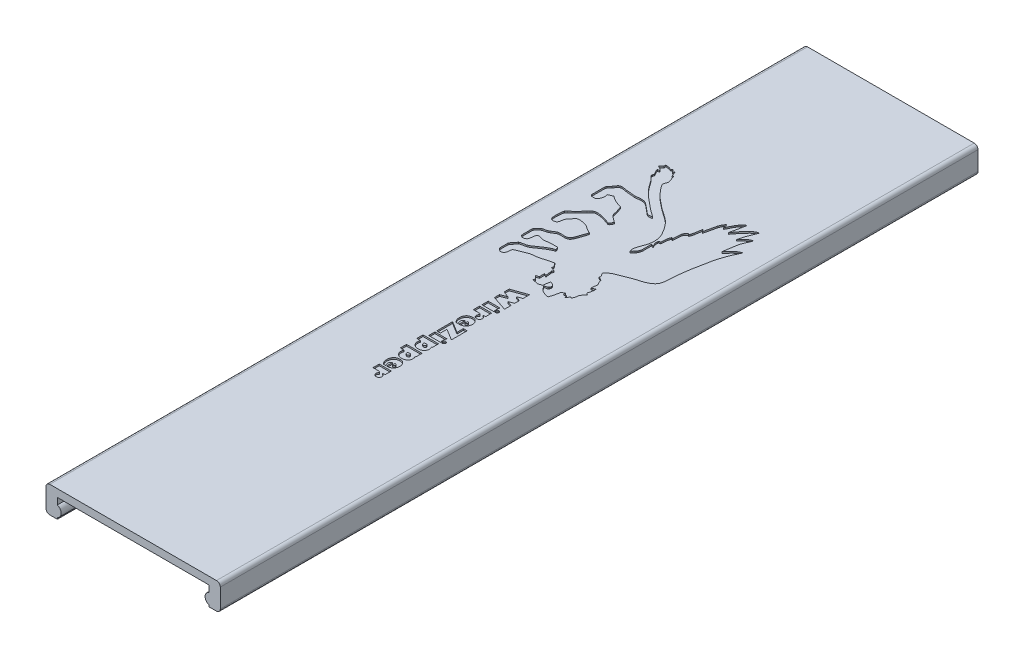
SolidWorks part; units mm, degrees
ref_plane "Front Plane" through (0, 0, 0) normal (0, 0, 1) x (1, 0, 0)
ref_plane "Top Plane" through (0, 0, 0) normal (0, 1, 0) x (1, 0, 0)
ref_plane "Right Plane" through (0, 0, 0) normal (1, 0, 0) x (0, 0, -1)
sketch "Sketch1" plane through (0, 0, 0) normal (0, 0, 1) x (1, 0, 0)
  line L0 (21.5, 0) -> (22.5, 0)
  line L1 (0.5, 0) -> (1.5, 0)
  line L2 (0, 0.5) -> (0, 3)
  line L3 (0.5, 3.5) -> (22.5, 3.5)
  line L4 (23, 0.5) -> (23, 3)
  line L5 (1.5, 2.5) -> (21.5, 2.5)
  line L6 (1.5, 2.5) -> (1.5, 1.637)
  line L8 (21.5, 2.5) -> (21.5, 1.637)
  line L9 (1.5, 0.2228) -> (1.5, 0)
  line L10 (1.25, 0.9299) -> (21.75, 0.9299) construction
  line L11 (21.5, 0.2228) -> (21.5, 0)
  arc A1 (1.5, 0.2228) -> (1.5, 1.637) centre (1.25, 0.9299) ccw
  arc A2 (21.5, 1.637) -> (21.5, 0.2228) centre (21.75, 0.9299) ccw
  arc A3 (23, 3) -> (22.5, 3.5) centre (22.5, 3) ccw
  arc A4 (0.5, 3.5) -> (0, 3) centre (0.5, 3) ccw
  arc A5 (23, 0.5) -> (22.5, 0) centre (22.5, 0.5) cw
  arc A6 (0, 0.5) -> (0.5, 0) centre (0.5, 0.5) ccw
  point P9 (11.5, 2.5)
  point P10 (11.5, 3.5)
  point P11 (0, 1.75)
  point P20 (23, 3.5)
  point P23 (0, 3.5)
  point P28 (0, 0)
  dimension "D6" = 1.5
  dimension "D9" = 0.5
  dimension "D10" = 0.5
  dimension "D1" = 23
  dimension "D2" = 3.5
  dimension "D3" = 1
  dimension "D4" = 1.5
  dimension "D5" = 20
  dimension "D7" = 0.25
  dimension "D8" = 0.25
extrude "Boss-Extrude1" add sketch "Sketch1" along normal blind 100
sketch "Sketch2" plane through (0, 3.5, -40.204) normal (0, 1, 0) x (1, 0, 0)
  line L4 (19.7713, -68.0162) -> (19.7056, -68.0387)
  line L5 (19.7056, -68.0387) -> (19.6414, -68.0638)
  line L6 (19.6414, -68.0638) -> (19.5786, -68.0912)
  line L7 (19.5786, -68.0912) -> (19.5173, -68.1208)
  line L8 (19.5173, -68.1208) -> (19.4572, -68.1527)
  line L9 (19.4572, -68.1527) -> (19.3985, -68.1865)
  line L10 (19.3985, -68.1865) -> (19.341, -68.2223)
  line L11 (19.341, -68.2223) -> (19.2846, -68.2598)
  line L12 (19.2846, -68.2598) -> (19.2294, -68.2991)
  line L13 (19.2294, -68.2991) -> (19.1752, -68.34)
  line L14 (19.1752, -68.34) -> (19.122, -68.3824)
  line L15 (19.122, -68.3824) -> (19.0697, -68.4261)
  line L16 (19.0697, -68.4261) -> (19.0184, -68.4711)
  line L17 (19.0184, -68.4711) -> (18.918, -68.5644)
  line L18 (18.918, -68.5644) -> (18.7727, -68.711)
  line L19 (18.7727, -68.711) -> (18.2698, -69.2714)
  line L20 (18.2698, -69.2714) -> (18.2812, -69.1529)
  line L21 (18.2812, -69.1529) -> (18.535, -67.5691)
  line L22 (18.535, -67.5691) -> (18.544, -67.5095)
  line L23 (18.544, -67.5095) -> (18.5547, -67.4504)
  line L24 (18.5547, -67.4504) -> (18.567, -67.3918)
  line L25 (18.567, -67.3918) -> (18.5808, -67.3338)
  line L26 (18.5808, -67.3338) -> (18.6125, -67.2189)
  line L27 (18.6125, -67.2189) -> (18.649, -67.1057)
  line L28 (18.649, -67.1057) -> (18.7112, -66.9383)
  line L29 (18.7112, -66.9383) -> (19.0474, -66.172)
  line L30 (19.0474, -66.172) -> (19.1337, -65.9499)
  line L31 (19.1337, -65.9499) -> (19.0766, -65.96)
  line L32 (19.0766, -65.96) -> (19.021, -65.9729)
  line L33 (19.021, -65.9729) -> (18.9668, -65.9885)
  line L34 (18.9668, -65.9885) -> (18.9139, -66.0067)
  line L35 (18.9139, -66.0067) -> (18.8624, -66.0273)
  line L36 (18.8624, -66.0273) -> (18.812, -66.0502)
  line L37 (18.812, -66.0502) -> (18.7628, -66.0753)
  line L38 (18.7628, -66.0753) -> (18.7147, -66.1024)
  line L39 (18.7147, -66.1024) -> (18.6677, -66.1313)
  line L40 (18.6677, -66.1313) -> (18.6216, -66.1621)
  line L41 (18.6216, -66.1621) -> (18.5764, -66.1944)
  line L42 (18.5764, -66.1944) -> (18.5321, -66.2282)
  line L43 (18.5321, -66.2282) -> (18.4458, -66.2997)
  line L44 (18.4458, -66.2997) -> (18.3621, -66.3754)
  line L45 (18.3621, -66.3754) -> (18.2006, -66.5354)
  line L46 (18.2006, -66.5354) -> (17.8477, -66.8963)
  line L47 (17.8477, -66.8963) -> (17.8847, -66.737)
  line L48 (17.8847, -66.737) -> (17.9683, -66.4211)
  line L49 (17.9683, -66.4211) -> (18.0638, -66.1089)
  line L50 (18.0638, -66.1089) -> (18.226, -65.6467)
  line L51 (18.226, -65.6467) -> (18.633, -64.6662)
  line L52 (18.633, -64.6662) -> (18.5994, -64.6698)
  line L53 (18.5994, -64.6698) -> (18.5332, -64.6806)
  line L54 (18.5332, -64.6806) -> (18.4685, -64.6959)
  line L55 (18.4685, -64.6959) -> (18.4051, -64.7155)
  line L56 (18.4051, -64.7155) -> (18.3126, -64.752)
  line L57 (18.3126, -64.752) -> (18.2231, -64.7961)
  line L58 (18.2231, -64.7961) -> (18.0805, -64.8835)
  line L59 (18.0805, -64.8835) -> (17.7942, -65.1134)
  line L60 (17.7942, -65.1134) -> (17.0691, -65.9091)
  line L61 (17.0691, -65.9091) -> (16.8287, -66.2416)
  line L62 (16.8287, -66.2416) -> (16.513, -66.6563)
  line L63 (16.513, -66.6563) -> (16.7942, -65.369)
  line L64 (16.7942, -65.369) -> (16.9419, -64.5963)
  line L65 (16.9419, -64.5963) -> (16.8708, -64.6363)
  line L66 (16.8708, -64.6363) -> (16.8028, -64.6792)
  line L67 (16.8028, -64.6792) -> (16.7378, -64.7251)
  line L68 (16.7378, -64.7251) -> (16.6757, -64.7737)
  line L69 (16.6757, -64.7737) -> (16.6162, -64.8249)
  line L70 (16.6162, -64.8249) -> (16.5593, -64.8785)
  line L71 (16.5593, -64.8785) -> (16.5048, -64.9343)
  line L72 (16.5048, -64.9343) -> (16.4525, -64.9923)
  line L73 (16.4525, -64.9923) -> (16.4023, -65.0522)
  line L74 (16.4023, -65.0522) -> (16.3541, -65.114)
  line L75 (16.3541, -65.114) -> (16.3077, -65.1774)
  line L76 (16.3077, -65.1774) -> (16.263, -65.2423)
  line L77 (16.263, -65.2423) -> (16.2198, -65.3086)
  line L78 (16.2198, -65.3086) -> (16.178, -65.3761)
  line L79 (16.178, -65.3761) -> (16.0979, -65.514)
  line L80 (16.0979, -65.514) -> (15.9845, -65.7262)
  line L81 (15.9845, -65.7262) -> (15.694, -66.2934)
  line L82 (15.694, -66.2934) -> (15.6177, -66.4289)
  line L83 (15.6177, -66.4289) -> (15.549, -65.8484)
  line L84 (15.549, -65.8484) -> (15.5225, -65.8651)
  line L85 (15.5225, -65.8651) -> (15.4723, -65.9013)
  line L86 (15.4723, -65.9013) -> (15.426, -65.9412)
  line L87 (15.426, -65.9412) -> (15.3833, -65.9844)
  line L88 (15.3833, -65.9844) -> (15.3439, -66.0306)
  line L89 (15.3439, -66.0306) -> (15.2905, -66.1046)
  line L90 (15.2905, -66.1046) -> (15.2284, -66.2106)
  line L91 (15.2284, -66.2106) -> (15.0765, -66.58)
  line L92 (15.0765, -66.58) -> (15.0409, -66.6935)
  line L93 (15.0409, -66.6935) -> (14.6863, -68.2584)
  line L94 (14.6863, -68.2584) -> (14.4749, -67.9375)
  line L95 (14.4749, -67.9375) -> (14.4456, -68.1048)
  line L96 (14.4456, -68.1048) -> (14.3106, -68.9476)
  line L97 (14.3106, -68.9476) -> (14.2712, -69.1132)
  line L98 (14.2712, -69.1132) -> (14.24, -69.2224)
  line L99 (14.24, -69.2224) -> (14.2042, -69.3303)
  line L100 (14.2042, -69.3303) -> (14.1631, -69.4368)
  line L101 (14.1631, -69.4368) -> (14.1404, -69.4895)
  line L102 (14.1404, -69.4895) -> (14.1161, -69.5418)
  line L103 (14.1161, -69.5418) -> (13.9814, -69.4095)
  line L104 (13.9814, -69.4095) -> (13.7581, -69.6328)
  line L105 (13.7581, -69.6328) -> (13.6767, -69.7542)
  line L106 (13.6767, -69.7542) -> (13.6425, -69.8308)
  line L107 (13.6425, -69.8308) -> (13.6243, -69.8924)
  line L108 (13.6243, -69.8924) -> (13.6148, -69.9324)
  line L109 (13.6148, -69.9324) -> (13.592, -70.0527)
  line L110 (13.592, -70.0527) -> (13.5689, -70.255)
  line L111 (13.5689, -70.255) -> (13.5297, -71.0705)
  line L112 (13.5297, -71.0705) -> (13.3341, -70.9606)
  line L113 (13.3341, -70.9606) -> (13.3022, -71.0425)
  line L114 (13.3022, -71.0425) -> (13.248, -71.2091)
  line L115 (13.248, -71.2091) -> (13.2062, -71.3788)
  line L116 (13.2062, -71.3788) -> (13.1698, -71.5941)
  line L117 (13.1698, -71.5941) -> (13.1475, -71.8557)
  line L118 (13.1475, -71.8557) -> (13.1495, -72.206)
  line L119 (13.1495, -72.206) -> (12.9637, -72.2453)
  line L120 (12.9637, -72.2453) -> (12.9195, -72.274)
  line L121 (12.9195, -72.274) -> (12.8989, -72.299)
  line L122 (12.8989, -72.299) -> (12.8883, -72.3195)
  line L123 (12.8883, -72.3195) -> (12.8805, -72.3435)
  line L124 (12.8805, -72.3435) -> (12.874, -72.3729)
  line L125 (12.874, -72.3729) -> (12.8656, -72.4318)
  line L126 (12.8656, -72.4318) -> (12.8625, -72.4903)
  line L127 (12.8625, -72.4903) -> (12.8643, -72.5487)
  line L128 (12.8643, -72.5487) -> (12.8705, -72.6068)
  line L129 (12.8705, -72.6068) -> (12.8937, -72.722)
  line L130 (12.8937, -72.722) -> (13.0558, -73.168)
  line L131 (13.0558, -73.168) -> (12.7626, -73.0589)
  line L132 (12.7626, -73.0589) -> (12.7728, -74.2235)
  line L133 (12.7728, -74.2235) -> (12.7694, -74.268)
  line L134 (12.7694, -74.268) -> (12.7642, -74.3119)
  line L135 (12.7642, -74.3119) -> (12.7573, -74.3554)
  line L136 (12.7573, -74.3554) -> (12.7487, -74.3983)
  line L137 (12.7487, -74.3983) -> (12.7384, -74.4406)
  line L138 (12.7384, -74.4406) -> (12.7265, -74.4825)
  line L139 (12.7265, -74.4825) -> (12.7131, -74.5237)
  line L140 (12.7131, -74.5237) -> (12.6982, -74.5644)
  line L141 (12.6982, -74.5644) -> (12.6819, -74.6046)
  line L142 (12.6819, -74.6046) -> (12.6642, -74.6441)
  line L143 (12.6642, -74.6441) -> (12.6248, -74.7214)
  line L144 (12.6248, -74.7214) -> (12.5806, -74.7963)
  line L145 (12.5806, -74.7963) -> (12.5319, -74.8686)
  line L146 (12.5319, -74.8686) -> (12.4791, -74.9384)
  line L147 (12.4791, -74.9384) -> (12.4226, -75.0055)
  line L148 (12.4226, -75.0055) -> (12.332, -75.1011)
  line L149 (12.332, -75.1011) -> (12.2356, -75.1902)
  line L150 (12.2356, -75.1902) -> (12.1347, -75.2728)
  line L151 (12.1347, -75.2728) -> (12.0463, -74.8208)
  line L152 (12.0463, -74.8208) -> (12.0572, -74.7514)
  line L153 (12.0572, -74.7514) -> (12.0701, -74.6825)
  line L154 (12.0701, -74.6825) -> (12.0846, -74.6141)
  line L155 (12.0846, -74.6141) -> (12.1008, -74.546)
  line L156 (12.1008, -74.546) -> (12.1374, -74.4111)
  line L157 (12.1374, -74.4111) -> (12.2004, -74.2109)
  line L158 (12.2004, -74.2109) -> (12.4552, -73.4833)
  line L159 (12.4552, -73.4833) -> (12.4951, -73.3494)
  line L160 (12.4951, -73.3494) -> (12.5302, -73.2142)
  line L161 (12.5302, -73.2142) -> (12.5455, -73.1461)
  line L162 (12.5455, -73.1461) -> (12.5591, -73.0775)
  line L163 (12.5591, -73.0775) -> (12.5709, -73.0084)
  line L164 (12.5709, -73.0084) -> (12.5807, -72.9388)
  line L165 (12.5807, -72.9388) -> (12.5884, -72.8687)
  line L166 (12.5884, -72.8687) -> (12.5946, -72.8106)
  line L167 (12.5946, -72.8106) -> (12.6038, -72.6941)
  line L168 (12.6038, -72.6941) -> (12.6085, -72.5773)
  line L169 (12.6085, -72.5773) -> (12.6087, -72.4603)
  line L170 (12.6087, -72.4603) -> (12.6042, -72.3433)
  line L171 (12.6042, -72.3433) -> (12.5951, -72.2267)
  line L172 (12.5951, -72.2267) -> (12.5813, -72.1106)
  line L173 (12.5813, -72.1106) -> (12.5626, -71.9952)
  line L174 (12.5626, -71.9952) -> (12.5392, -71.8808)
  line L175 (12.5392, -71.8808) -> (12.5108, -71.7675)
  line L176 (12.5108, -71.7675) -> (12.4775, -71.6556)
  line L177 (12.4775, -71.6556) -> (12.4392, -71.5453)
  line L178 (12.4392, -71.5453) -> (12.3958, -71.4368)
  line L179 (12.3958, -71.4368) -> (12.3473, -71.3303)
  line L180 (12.3473, -71.3303) -> (12.2936, -71.2261)
  line L181 (12.2936, -71.2261) -> (12.1536, -70.9726)
  line L182 (12.1536, -70.9726) -> (12.0556, -70.8056)
  line L183 (12.0556, -70.8056) -> (11.9537, -70.6406)
  line L184 (11.9537, -70.6406) -> (11.8476, -70.4782)
  line L185 (11.8476, -70.4782) -> (11.7372, -70.3187)
  line L186 (11.7372, -70.3187) -> (11.6223, -70.1625)
  line L187 (11.6223, -70.1625) -> (11.5631, -70.0859)
  line L188 (11.5631, -70.0859) -> (11.5027, -70.0102)
  line L189 (11.5027, -70.0102) -> (11.441, -69.9356)
  line L190 (11.441, -69.9356) -> (11.3782, -69.8621)
  line L191 (11.3782, -69.8621) -> (11.3141, -69.7897)
  line L192 (11.3141, -69.7897) -> (11.2486, -69.7186)
  line L193 (11.2486, -69.7186) -> (11.1819, -69.6487)
  line L194 (11.1819, -69.6487) -> (11.1139, -69.5802)
  line L195 (11.1139, -69.5802) -> (11.0445, -69.513)
  line L196 (11.0445, -69.513) -> (10.9737, -69.4473)
  line L197 (10.9737, -69.4473) -> (10.9015, -69.383)
  line L198 (10.9015, -69.383) -> (10.8279, -69.3203)
  line L199 (10.8279, -69.3203) -> (10.7528, -69.2592)
  line L200 (10.7528, -69.2592) -> (10.6763, -69.1997)
  line L201 (10.6763, -69.1997) -> (10.5982, -69.1419)
  line L202 (10.5982, -69.1419) -> (10.5187, -69.0859)
  line L203 (10.5187, -69.0859) -> (9.4452, -68.33)
  line L204 (9.4452, -68.33) -> (9.3773, -68.2867)
  line L205 (9.3773, -68.2867) -> (8.53, -67.6115)
  line L206 (8.53, -67.6115) -> (8.3361, -67.4547)
  line L207 (8.3361, -67.4547) -> (8.1475, -67.2919)
  line L208 (8.1475, -67.2919) -> (7.9041, -67.0658)
  line L209 (7.9041, -67.0658) -> (7.6696, -66.8305)
  line L210 (7.6696, -66.8305) -> (7.4436, -66.5867)
  line L211 (7.4436, -66.5867) -> (7.173, -66.2715)
  line L212 (7.173, -66.2715) -> (6.8648, -65.88)
  line L213 (6.8648, -65.88) -> (6.7097, -65.6569)
  line L214 (6.7097, -65.6569) -> (6.6566, -65.5438)
  line L215 (6.6566, -65.5438) -> (6.6407, -65.4743)
  line L216 (6.6407, -65.4743) -> (6.638, -65.4193)
  line L217 (6.638, -65.4193) -> (6.637, -65.3934)
  line L218 (6.637, -65.3934) -> (6.6379, -65.3678)
  line L219 (6.6379, -65.3678) -> (6.6403, -65.3423)
  line L220 (6.6403, -65.3423) -> (6.6494, -65.2922)
  line L221 (6.6494, -65.2922) -> (6.6631, -65.2427)
  line L222 (6.6631, -65.2427) -> (6.7675, -64.9759)
  line L223 (6.7675, -64.9759) -> (6.7877, -64.9024)
  line L224 (6.7877, -64.9024) -> (6.7953, -64.8526)
  line L225 (6.7953, -64.8526) -> (6.7968, -64.8275)
  line L226 (6.7968, -64.8275) -> (6.7967, -64.8021)
  line L227 (6.7967, -64.8021) -> (6.7947, -64.7765)
  line L228 (6.7947, -64.7765) -> (6.7907, -64.7506)
  line L229 (6.7907, -64.7506) -> (6.7846, -64.7245)
  line L230 (6.7846, -64.7245) -> (6.7763, -64.698)
  line L231 (6.7763, -64.698) -> (6.4789, -63.8339)
  line L232 (6.4789, -63.8339) -> (6.3162, -63.8719)
  line L233 (6.3162, -63.8719) -> (6.0814, -63.2667)
  line L234 (6.0814, -63.2667) -> (5.9437, -63.4423)
  line L235 (5.9437, -63.4423) -> (5.6179, -63.0803)
  line L236 (5.6179, -63.0803) -> (5.4993, -63.2471)
  line L237 (5.4993, -63.2471) -> (5.4182, -63.2127)
  line L238 (5.4182, -63.2127) -> (5.0832, -63.1098)
  line L239 (5.0832, -63.1098) -> (4.852, -63.0789)
  line L240 (4.852, -63.0789) -> (4.6755, -63.0793)
  line L241 (4.6755, -63.0793) -> (4.6672, -63.3323)
  line L242 (4.6672, -63.3323) -> (4.3029, -63.6837)
  line L243 (4.3029, -63.6837) -> (4.4364, -63.7454)
  line L244 (4.4364, -63.7454) -> (4.6822, -63.862)
  line L245 (4.6822, -63.862) -> (4.7406, -63.904)
  line L246 (4.7406, -63.904) -> (4.7757, -63.9362)
  line L247 (4.7757, -63.9362) -> (4.8071, -63.9724)
  line L248 (4.8071, -63.9724) -> (4.8213, -63.9922)
  line L249 (4.8213, -63.9922) -> (4.8345, -64.0131)
  line L250 (4.8345, -64.0131) -> (4.8464, -64.0354)
  line L251 (4.8464, -64.0354) -> (4.8571, -64.059)
  line L252 (4.8571, -64.059) -> (4.8666, -64.0839)
  line L253 (4.8666, -64.0839) -> (4.6194, -64.1381)
  line L254 (4.6194, -64.1381) -> (4.6364, -64.2183)
  line L255 (4.6364, -64.2183) -> (4.6966, -64.3979)
  line L256 (4.6966, -64.3979) -> (4.9547, -64.8424)
  line L257 (4.9547, -64.8424) -> (4.8825, -65.0571)
  line L258 (4.8825, -65.0571) -> (4.8809, -65.1758)
  line L259 (4.8809, -65.1758) -> (4.9013, -65.2205)
  line L260 (4.9013, -65.2205) -> (4.9626, -65.3253)
  line L261 (4.9626, -65.3253) -> (5.3289, -65.7142)
  line L262 (5.3289, -65.7142) -> (5.3543, -65.7372)
  line L263 (5.3543, -65.7372) -> (5.4262, -65.8098)
  line L264 (5.4262, -65.8098) -> (5.5342, -65.9403)
  line L265 (5.5342, -65.9403) -> (5.9242, -66.4974)
  line L266 (5.9242, -66.4974) -> (5.9941, -66.5912)
  line L267 (5.9941, -66.5912) -> (6.0655, -66.6837)
  line L268 (6.0655, -66.6837) -> (6.1382, -66.7749)
  line L269 (6.1382, -66.7749) -> (6.2123, -66.8649)
  line L270 (6.2123, -66.8649) -> (6.2877, -66.9537)
  line L271 (6.2877, -66.9537) -> (6.3643, -67.0414)
  line L272 (6.3643, -67.0414) -> (6.4422, -67.128)
  line L273 (6.4422, -67.128) -> (6.5212, -67.2135)
  line L274 (6.5212, -67.2135) -> (6.6012, -67.2979)
  line L275 (6.6012, -67.2979) -> (6.7645, -67.4639)
  line L276 (6.7645, -67.4639) -> (6.9315, -67.6263)
  line L277 (6.9315, -67.6263) -> (7.102, -67.7852)
  line L278 (7.102, -67.7852) -> (7.2754, -67.9411)
  line L279 (7.2754, -67.9411) -> (7.5403, -68.1699)
  line L280 (7.5403, -68.1699) -> (8.3562, -68.8291)
  line L281 (8.3562, -68.8291) -> (8.3997, -68.8707)
  line L282 (8.3997, -68.8707) -> (8.4887, -68.9512)
  line L283 (8.4887, -68.9512) -> (8.6269, -69.0657)
  line L284 (8.6269, -69.0657) -> (8.9149, -69.2793)
  line L285 (8.9149, -69.2793) -> (9.5957, -69.7675)
  line L286 (9.5957, -69.7675) -> (9.7335, -69.883)
  line L287 (9.7335, -69.883) -> (9.2384, -69.9121)
  line L288 (9.2384, -69.9121) -> (9.1226, -69.8981)
  line L289 (9.1226, -69.8981) -> (9.0543, -69.8802)
  line L290 (9.0543, -69.8802) -> (8.9059, -69.7676)
  line L291 (8.9059, -69.7676) -> (7.9015, -68.9336)
  line L292 (7.9015, -68.9336) -> (7.6513, -68.7497)
  line L293 (7.6513, -68.7497) -> (7.6022, -68.7188)
  line L294 (7.6022, -68.7188) -> (7.5523, -68.6913)
  line L295 (7.5523, -68.6913) -> (7.5017, -68.667)
  line L296 (7.5017, -68.667) -> (7.4505, -68.6458)
  line L297 (7.4505, -68.6458) -> (7.3986, -68.6275)
  line L298 (7.3986, -68.6275) -> (7.3462, -68.612)
  line L299 (7.3462, -68.612) -> (7.2932, -68.599)
  line L300 (7.2932, -68.599) -> (7.2397, -68.5885)
  line L301 (7.2397, -68.5885) -> (7.1858, -68.5802)
  line L302 (7.1858, -68.5802) -> (7.1315, -68.5739)
  line L303 (7.1315, -68.5739) -> (7.0768, -68.5696)
  line L304 (7.0768, -68.5696) -> (7.0217, -68.5671)
  line L305 (7.0217, -68.5671) -> (6.9108, -68.5665)
  line L306 (6.9108, -68.5665) -> (6.7431, -68.5748)
  line L307 (6.7431, -68.5748) -> (6.1852, -68.6265)
  line L308 (6.1852, -68.6265) -> (6.0763, -68.6314)
  line L309 (6.0763, -68.6314) -> (4.992, -68.5326)
  line L310 (4.992, -68.5326) -> (4.8611, -68.5147)
  line L311 (4.8611, -68.5147) -> (4.3666, -68.4393)
  line L312 (4.3666, -68.4393) -> (4.2677, -68.4378)
  line L313 (4.2677, -68.4378) -> (4.2019, -68.4418)
  line L314 (4.2019, -68.4418) -> (4.1362, -68.4506)
  line L315 (4.1362, -68.4506) -> (4.0706, -68.4648)
  line L316 (4.0706, -68.4648) -> (4.0379, -68.4741)
  line L317 (4.0379, -68.4741) -> (4.014, -68.4828)
  line L318 (4.014, -68.4828) -> (3.9912, -68.4926)
  line L319 (3.9912, -68.4926) -> (3.9694, -68.5037)
  line L320 (3.9694, -68.5037) -> (3.9287, -68.5289)
  line L321 (3.9287, -68.5289) -> (3.8914, -68.5581)
  line L322 (3.8914, -68.5581) -> (3.857, -68.5905)
  line L323 (3.857, -68.5905) -> (3.7809, -68.6828)
  line L324 (3.7809, -68.6828) -> (3.575, -68.9832)
  line L325 (3.575, -68.9832) -> (3.5102, -69.0651)
  line L326 (3.5102, -69.0651) -> (3.2556, -69.3376)
  line L327 (3.2556, -69.3376) -> (3.2114, -69.4017)
  line L328 (3.2114, -69.4017) -> (3.1867, -69.4471)
  line L329 (3.1867, -69.4471) -> (3.1668, -69.4951)
  line L330 (3.1668, -69.4951) -> (3.1589, -69.5201)
  line L331 (3.1589, -69.5201) -> (3.1524, -69.5459)
  line L332 (3.1524, -69.5459) -> (3.1474, -69.5726)
  line L333 (3.1474, -69.5726) -> (3.144, -69.6001)
  line L334 (3.144, -69.6001) -> (3.14, -69.6565)
  line L335 (3.14, -69.6565) -> (3.1406, -71.2386)
  line L336 (3.1406, -71.2386) -> (3.1441, -71.2775)
  line L337 (3.1441, -71.2775) -> (3.1837, -71.4053)
  line L338 (3.1837, -71.4053) -> (3.2293, -71.4697)
  line L339 (3.2293, -71.4697) -> (3.2692, -71.5026)
  line L340 (3.2692, -71.5026) -> (3.3044, -71.5205)
  line L341 (3.3044, -71.5205) -> (3.3442, -71.5313)
  line L342 (3.3442, -71.5313) -> (3.6184, -71.552)
  line L343 (3.6184, -71.552) -> (3.7097, -71.5433)
  line L344 (3.7097, -71.5433) -> (3.7753, -71.5281)
  line L345 (3.7753, -71.5281) -> (3.8171, -71.513)
  line L346 (3.8171, -71.513) -> (3.857, -71.4934)
  line L347 (3.857, -71.4934) -> (3.8945, -71.4689)
  line L348 (3.8945, -71.4689) -> (3.9123, -71.4547)
  line L349 (3.9123, -71.4547) -> (3.9294, -71.4391)
  line L350 (3.9294, -71.4391) -> (3.9457, -71.422)
  line L351 (3.9457, -71.422) -> (3.9613, -71.4035)
  line L352 (3.9613, -71.4035) -> (3.9894, -71.3736)
  line L353 (3.9894, -71.3736) -> (4.0159, -71.3428)
  line L354 (4.0159, -71.3428) -> (4.0409, -71.3111)
  line L355 (4.0409, -71.3111) -> (4.0643, -71.2784)
  line L356 (4.0643, -71.2784) -> (4.0862, -71.2449)
  line L357 (4.0862, -71.2449) -> (4.1066, -71.2106)
  line L358 (4.1066, -71.2106) -> (4.1255, -71.1756)
  line L359 (4.1255, -71.1756) -> (4.1429, -71.1399)
  line L360 (4.1429, -71.1399) -> (4.1588, -71.1035)
  line L361 (4.1588, -71.1035) -> (4.1732, -71.0666)
  line L362 (4.1732, -71.0666) -> (4.1862, -71.0291)
  line L363 (4.1862, -71.0291) -> (4.1977, -70.9912)
  line L364 (4.1977, -70.9912) -> (4.2078, -70.9528)
  line L365 (4.2078, -70.9528) -> (4.2164, -70.914)
  line L366 (4.2164, -70.914) -> (4.2236, -70.8749)
  line L367 (4.2236, -70.8749) -> (4.2338, -70.7958)
  line L368 (4.2338, -70.7958) -> (4.2385, -70.7161)
  line L369 (4.2385, -70.7161) -> (4.2376, -70.636)
  line L370 (4.2376, -70.636) -> (4.2314, -70.556)
  line L371 (4.2314, -70.556) -> (4.2198, -70.4765)
  line L372 (4.2198, -70.4765) -> (4.203, -70.3979)
  line L373 (4.203, -70.3979) -> (4.181, -70.3206)
  line L374 (4.181, -70.3206) -> (4.7901, -70.0484)
  line L375 (4.7901, -70.0484) -> (5.2245, -70.3466)
  line L376 (5.2245, -70.3466) -> (5.4751, -70.4867)
  line L377 (5.4751, -70.4867) -> (5.6484, -70.5673)
  line L378 (5.6484, -70.5673) -> (5.7819, -70.6197)
  line L379 (5.7819, -70.6197) -> (5.9186, -70.6643)
  line L380 (5.9186, -70.6643) -> (6.0116, -70.6894)
  line L381 (6.0116, -70.6894) -> (6.4412, -70.8042)
  line L382 (6.4412, -70.8042) -> (6.6803, -71.4735)
  line L383 (6.6803, -71.4735) -> (6.7004, -71.5284)
  line L384 (6.7004, -71.5284) -> (6.7442, -71.699)
  line L385 (6.7442, -71.699) -> (6.8306, -72.1014)
  line L386 (6.8306, -72.1014) -> (6.8618, -72.1829)
  line L387 (6.8618, -72.1829) -> (6.8877, -72.2354)
  line L388 (6.8877, -72.2354) -> (6.9183, -72.2862)
  line L389 (6.9183, -72.2862) -> (6.9701, -72.3445)
  line L390 (6.9701, -72.3445) -> (7.1086, -72.4804)
  line L391 (7.1086, -72.4804) -> (7.7939, -72.9919)
  line L392 (7.7939, -72.9919) -> (7.7351, -73.1517)
  line L393 (7.7351, -73.1517) -> (7.6452, -73.3187)
  line L394 (7.6452, -73.3187) -> (7.5925, -73.3834)
  line L395 (7.5925, -73.3834) -> (7.5465, -73.4263)
  line L396 (7.5465, -73.4263) -> (7.4942, -73.4637)
  line L397 (7.4942, -73.4637) -> (7.4555, -73.4852)
  line L398 (7.4555, -73.4852) -> (6.9853, -73.3177)
  line L399 (6.9853, -73.3177) -> (6.4139, -73.1402)
  line L400 (6.4139, -73.1402) -> (6.2188, -73.0984)
  line L401 (6.2188, -73.0984) -> (6.0703, -73.0755)
  line L402 (6.0703, -73.0755) -> (6.002, -73.0661)
  line L403 (6.002, -73.0661) -> (5.6117, -73.0217)
  line L404 (5.6117, -73.0217) -> (5.5053, -73.0221)
  line L405 (5.5053, -73.0221) -> (5.4354, -73.0278)
  line L406 (5.4354, -73.0278) -> (5.3668, -73.0388)
  line L407 (5.3668, -73.0388) -> (5.3331, -73.0464)
  line L408 (5.3331, -73.0464) -> (5.2997, -73.0557)
  line L409 (5.2997, -73.0557) -> (5.2669, -73.0666)
  line L410 (5.2669, -73.0666) -> (5.2345, -73.0793)
  line L411 (5.2345, -73.0793) -> (5.2027, -73.0938)
  line L412 (5.2027, -73.0938) -> (5.1715, -73.1103)
  line L413 (5.1715, -73.1103) -> (5.1409, -73.1288)
  line L414 (5.1409, -73.1288) -> (5.111, -73.1495)
  line L415 (5.111, -73.1495) -> (5.0818, -73.1724)
  line L416 (5.0818, -73.1724) -> (5.0388, -73.2082)
  line L417 (5.0388, -73.2082) -> (4.9143, -73.3196)
  line L418 (4.9143, -73.3196) -> (4.7183, -73.5171)
  line L419 (4.7183, -73.5171) -> (3.986, -74.3579)
  line L420 (3.986, -74.3579) -> (3.4335, -74.7985)
  line L421 (3.4335, -74.7985) -> (3.2432, -74.9884)
  line L422 (3.2432, -74.9884) -> (3.2042, -75.1321)
  line L423 (3.2042, -75.1321) -> (3.1326, -75.8459)
  line L424 (3.1326, -75.8459) -> (3.1308, -76.2528)
  line L425 (3.1308, -76.2528) -> (3.1487, -76.422)
  line L426 (3.1487, -76.422) -> (3.1689, -76.5211)
  line L427 (3.1689, -76.5211) -> (3.1872, -76.5856)
  line L428 (3.1872, -76.5856) -> (3.2098, -76.6487)
  line L429 (3.2098, -76.6487) -> (3.2373, -76.71)
  line L430 (3.2373, -76.71) -> (3.2699, -76.7694)
  line L431 (3.2699, -76.7694) -> (3.2883, -76.7983)
  line L432 (3.2883, -76.7983) -> (3.3292, -76.819)
  line L433 (3.3292, -76.819) -> (3.3932, -76.8429)
  line L434 (3.3932, -76.8429) -> (3.4598, -76.8586)
  line L435 (3.4598, -76.8586) -> (3.5512, -76.8679)
  line L436 (3.5512, -76.8679) -> (3.644, -76.8649)
  line L437 (3.644, -76.8649) -> (3.7814, -76.8404)
  line L438 (3.7814, -76.8404) -> (3.9314, -76.7866)
  line L439 (3.9314, -76.7866) -> (3.9502, -76.7698)
  line L440 (3.9502, -76.7698) -> (3.9676, -76.7523)
  line L441 (3.9676, -76.7523) -> (3.9837, -76.7339)
  line L442 (3.9837, -76.7339) -> (4.012, -76.6951)
  line L443 (4.012, -76.6951) -> (4.0358, -76.6537)
  line L444 (4.0358, -76.6537) -> (4.0557, -76.6102)
  line L445 (4.0557, -76.6102) -> (4.0855, -76.5179)
  line L446 (4.0855, -76.5179) -> (4.1545, -76.1303)
  line L447 (4.1545, -76.1303) -> (4.1578, -76.0999)
  line L448 (4.1578, -76.0999) -> (4.1626, -76.0703)
  line L449 (4.1626, -76.0703) -> (4.169, -76.0415)
  line L450 (4.169, -76.0415) -> (4.1769, -76.0135)
  line L451 (4.1769, -76.0135) -> (4.1968, -75.9596)
  line L452 (4.1968, -75.9596) -> (4.2214, -75.9082)
  line L453 (4.2214, -75.9082) -> (4.2658, -75.8349)
  line L454 (4.2658, -75.8349) -> (4.4881, -75.5651)
  line L455 (4.4881, -75.5651) -> (4.5925, -75.4268)
  line L456 (4.5925, -75.4268) -> (4.7686, -75.1769)
  line L457 (4.7686, -75.1769) -> (4.8234, -75.1263)
  line L458 (4.8234, -75.1263) -> (4.8698, -75.0957)
  line L459 (4.8698, -75.0957) -> (4.9038, -75.0796)
  line L460 (4.9038, -75.0796) -> (4.9405, -75.0674)
  line L461 (4.9405, -75.0674) -> (4.9801, -75.0596)
  line L462 (4.9801, -75.0596) -> (5.022, -75.0473)
  line L463 (5.022, -75.0473) -> (5.0638, -75.037)
  line L464 (5.0638, -75.037) -> (5.1057, -75.0287)
  line L465 (5.1057, -75.0287) -> (5.1475, -75.0223)
  line L466 (5.1475, -75.0223) -> (5.1893, -75.0177)
  line L467 (5.1893, -75.0177) -> (5.2311, -75.0147)
  line L468 (5.2311, -75.0147) -> (5.2729, -75.0134)
  line L469 (5.2729, -75.0134) -> (5.3147, -75.0136)
  line L470 (5.3147, -75.0136) -> (5.3982, -75.018)
  line L471 (5.3982, -75.018) -> (5.4815, -75.0273)
  line L472 (5.4815, -75.0273) -> (5.6062, -75.0489)
  line L473 (5.6062, -75.0489) -> (6.1798, -75.2004)
  line L474 (6.1798, -75.2004) -> (6.2396, -75.2191)
  line L475 (6.2396, -75.2191) -> (6.297, -75.2424)
  line L476 (6.297, -75.2424) -> (6.379, -75.2844)
  line L477 (6.379, -75.2844) -> (6.5333, -75.3862)
  line L478 (6.5333, -75.3862) -> (6.8623, -75.6178)
  line L479 (6.8623, -75.6178) -> (6.945, -75.6597)
  line L480 (6.945, -75.6597) -> (7.3529, -75.8473)
  line L481 (7.3529, -75.8473) -> (7.3353, -75.9277)
  line L482 (7.3353, -75.9277) -> (7.2542, -76.2027)
  line L483 (7.2542, -76.2027) -> (6.9853, -76.977)
  line L484 (6.9853, -76.977) -> (6.9218, -77.1748)
  line L485 (6.9218, -77.1748) -> (6.8417, -77.3713)
  line L486 (6.8417, -77.3713) -> (6.7927, -77.4646)
  line L487 (6.7927, -77.4646) -> (6.7559, -77.5237)
  line L488 (6.7559, -77.5237) -> (6.7156, -77.5798)
  line L489 (6.7156, -77.5798) -> (6.6712, -77.6323)
  line L490 (6.6712, -77.6323) -> (6.6474, -77.657)
  line L491 (6.6474, -77.657) -> (6.6225, -77.6807)
  line L492 (6.6225, -77.6807) -> (6.5965, -77.7032)
  line L493 (6.5965, -77.7032) -> (6.5693, -77.7244)
  line L494 (6.5693, -77.7244) -> (6.5408, -77.7444)
  line L495 (6.5408, -77.7444) -> (6.5111, -77.7629)
  line L496 (6.5111, -77.7629) -> (6.48, -77.7801)
  line L497 (6.48, -77.7801) -> (6.4476, -77.7958)
  line L498 (6.4476, -77.7958) -> (6.4056, -77.8087)
  line L499 (6.4056, -77.8087) -> (6.3634, -77.8195)
  line L500 (6.3634, -77.8195) -> (6.3211, -77.8286)
  line L501 (6.3211, -77.8286) -> (6.2785, -77.8359)
  line L502 (6.2785, -77.8359) -> (6.2358, -77.8416)
  line L503 (6.2358, -77.8416) -> (6.15, -77.849)
  line L504 (6.15, -77.849) -> (6.0204, -77.8517)
  line L505 (6.0204, -77.8517) -> (5.5419, -77.8342)
  line L506 (5.5419, -77.8342) -> (5.4122, -77.8386)
  line L507 (5.4122, -77.8386) -> (5.3262, -77.8475)
  line L508 (5.3262, -77.8475) -> (5.2834, -77.8541)
  line L509 (5.2834, -77.8541) -> (5.2408, -77.8624)
  line L510 (5.2408, -77.8624) -> (5.1984, -77.8725)
  line L511 (5.1984, -77.8725) -> (5.1429, -77.8929)
  line L512 (5.1429, -77.8929) -> (5.0372, -77.9432)
  line L513 (5.0372, -77.9432) -> (4.5955, -78.2327)
  line L514 (4.5955, -78.2327) -> (4.4658, -78.3013)
  line L515 (4.4658, -78.3013) -> (4.4141, -78.3286)
  line L516 (4.4141, -78.3286) -> (4.3608, -78.3512)
  line L517 (4.3608, -78.3512) -> (4.2508, -78.3859)
  line L518 (4.2508, -78.3859) -> (3.8549, -78.4745)
  line L519 (3.8549, -78.4745) -> (3.7737, -78.504)
  line L520 (3.7737, -78.504) -> (3.7213, -78.5287)
  line L521 (3.7213, -78.5287) -> (3.6706, -78.5583)
  line L522 (3.6706, -78.5583) -> (3.6162, -78.5953)
  line L523 (3.6162, -78.5953) -> (3.2174, -79.0006)
  line L524 (3.2174, -79.0006) -> (3.1932, -79.0363)
  line L525 (3.1932, -79.0363) -> (3.1737, -79.0734)
  line L526 (3.1737, -79.0734) -> (3.1523, -79.1314)
  line L527 (3.1523, -79.1314) -> (3.1358, -79.2122)
  line L528 (3.1358, -79.2122) -> (3.1303, -79.5906)
  line L529 (3.1303, -79.5906) -> (3.1317, -79.6254)
  line L530 (3.1317, -79.6254) -> (3.1352, -80.3612)
  line L531 (3.1352, -80.3612) -> (3.1532, -80.4995)
  line L532 (3.1532, -80.4995) -> (3.1755, -80.6021)
  line L533 (3.1755, -80.6021) -> (3.1949, -80.6327)
  line L534 (3.1949, -80.6327) -> (3.2166, -80.6607)
  line L535 (3.2166, -80.6607) -> (3.2403, -80.6861)
  line L536 (3.2403, -80.6861) -> (3.2659, -80.7089)
  line L537 (3.2659, -80.7089) -> (3.2932, -80.7292)
  line L538 (3.2932, -80.7292) -> (3.322, -80.747)
  line L539 (3.322, -80.747) -> (3.3522, -80.7624)
  line L540 (3.3522, -80.7624) -> (3.3836, -80.7752)
  line L541 (3.3836, -80.7752) -> (3.416, -80.7857)
  line L542 (3.416, -80.7857) -> (3.4492, -80.7938)
  line L543 (3.4492, -80.7938) -> (3.4831, -80.7995)
  line L544 (3.4831, -80.7995) -> (3.5175, -80.8029)
  line L545 (3.5175, -80.8029) -> (3.5521, -80.8041)
  line L546 (3.5521, -80.8041) -> (3.587, -80.8029)
  line L547 (3.587, -80.8029) -> (3.6217, -80.7995)
  line L548 (3.6217, -80.7995) -> (3.6563, -80.7939)
  line L549 (3.6563, -80.7939) -> (3.6905, -80.7862)
  line L550 (3.6905, -80.7862) -> (3.7241, -80.7762)
  line L551 (3.7241, -80.7762) -> (3.757, -80.7642)
  line L552 (3.757, -80.7642) -> (3.789, -80.7501)
  line L553 (3.789, -80.7501) -> (3.8199, -80.7339)
  line L554 (3.8199, -80.7339) -> (3.8495, -80.7157)
  line L555 (3.8495, -80.7157) -> (3.8777, -80.6955)
  line L556 (3.8777, -80.6955) -> (3.9043, -80.6733)
  line L557 (3.9043, -80.6733) -> (3.9291, -80.6492)
  line L558 (3.9291, -80.6492) -> (3.9519, -80.6232)
  line L559 (3.9519, -80.6232) -> (3.9726, -80.5953)
  line L560 (3.9726, -80.5953) -> (3.991, -80.5656)
  line L561 (3.991, -80.5656) -> (4.0069, -80.534)
  line L562 (4.0069, -80.534) -> (4.0267, -80.4685)
  line L563 (4.0267, -80.4685) -> (4.042, -80.4016)
  line L564 (4.042, -80.4016) -> (4.0936, -79.9875)
  line L565 (4.0936, -79.9875) -> (4.1181, -79.852)
  line L566 (4.1181, -79.852) -> (4.136, -79.7861)
  line L567 (4.136, -79.7861) -> (4.1589, -79.7219)
  line L568 (4.1589, -79.7219) -> (4.1725, -79.6905)
  line L569 (4.1725, -79.6905) -> (4.1877, -79.6596)
  line L570 (4.1877, -79.6596) -> (4.2046, -79.6293)
  line L571 (4.2046, -79.6293) -> (4.2234, -79.5996)
  line L572 (4.2234, -79.5996) -> (4.2441, -79.5705)
  line L573 (4.2441, -79.5705) -> (4.2943, -79.56)
  line L574 (4.2943, -79.56) -> (4.3945, -79.5495)
  line L575 (4.3945, -79.5495) -> (4.519, -79.5532)
  line L576 (4.519, -79.5532) -> (4.957, -79.6603)
  line L577 (4.957, -79.6603) -> (4.9931, -79.6704)
  line L578 (4.9931, -79.6704) -> (5.0293, -79.6788)
  line L579 (5.0293, -79.6788) -> (5.0656, -79.6855)
  line L580 (5.0656, -79.6855) -> (5.1018, -79.6907)
  line L581 (5.1018, -79.6907) -> (5.1381, -79.6943)
  line L582 (5.1381, -79.6943) -> (5.2106, -79.6976)
  line L583 (5.2106, -79.6976) -> (5.2833, -79.6962)
  line L584 (5.2833, -79.6962) -> (5.3923, -79.6872)
  line L585 (5.3923, -79.6872) -> (5.9018, -79.6117)
  line L586 (5.9018, -79.6117) -> (6.0109, -79.6057)
  line L587 (6.0109, -79.6057) -> (6.9107, -79.5831)
  line L588 (6.9107, -79.5831) -> (7.08, -79.9797)
  line L589 (7.08, -79.9797) -> (6.9606, -80.0183)
  line L590 (6.9606, -80.0183) -> (6.8433, -80.0615)
  line L591 (6.8433, -80.0615) -> (6.7277, -80.1089)
  line L592 (6.7277, -80.1089) -> (6.5577, -80.187)
  line L593 (6.5577, -80.187) -> (6.3912, -80.2727)
  line L594 (6.3912, -80.2727) -> (6.1741, -80.3968)
  line L595 (6.1741, -80.3968) -> (5.4975, -80.8472)
  line L596 (5.4975, -80.8472) -> (5.0502, -81.1631)
  line L597 (5.0502, -81.1631) -> (4.8455, -81.2766)
  line L598 (4.8455, -81.2766) -> (4.7027, -81.3392)
  line L599 (4.7027, -81.3392) -> (4.5918, -81.3776)
  line L600 (4.5918, -81.3776) -> (4.5159, -81.3986)
  line L601 (4.5159, -81.3986) -> (3.9625, -81.5099)
  line L602 (3.9625, -81.5099) -> (3.8363, -81.554)
  line L603 (3.8363, -81.554) -> (3.7636, -81.5898)
  line L604 (3.7636, -81.5898) -> (3.4218, -82.0245)
  line L605 (3.4218, -82.0245) -> (3.2301, -82.263)
  line L606 (3.2301, -82.263) -> (3.1896, -82.3412)
  line L607 (3.1896, -82.3412) -> (3.1742, -82.3919)
  line L608 (3.1742, -82.3919) -> (3.1686, -82.4276)
  line L609 (3.1686, -82.4276) -> (3.1671, -82.465)
  line L610 (3.1671, -82.465) -> (3.1691, -83.3694)
  line L611 (3.1691, -83.3694) -> (3.1712, -83.4048)
  line L612 (3.1712, -83.4048) -> (3.1763, -83.4397)
  line L613 (3.1763, -83.4397) -> (3.1842, -83.4741)
  line L614 (3.1842, -83.4741) -> (3.1949, -83.5078)
  line L615 (3.1949, -83.5078) -> (3.2082, -83.5406)
  line L616 (3.2082, -83.5406) -> (3.224, -83.5725)
  line L617 (3.224, -83.5725) -> (3.242, -83.6033)
  line L618 (3.242, -83.6033) -> (3.2621, -83.6329)
  line L619 (3.2621, -83.6329) -> (3.2842, -83.6612)
  line L620 (3.2842, -83.6612) -> (3.3082, -83.6881)
  line L621 (3.3082, -83.6881) -> (3.3338, -83.7133)
  line L622 (3.3338, -83.7133) -> (3.361, -83.7369)
  line L623 (3.361, -83.7369) -> (3.3895, -83.7587)
  line L624 (3.3895, -83.7587) -> (3.4193, -83.7786)
  line L625 (3.4193, -83.7786) -> (3.4502, -83.7964)
  line L626 (3.4502, -83.7964) -> (3.4819, -83.8121)
  line L627 (3.4819, -83.8121) -> (3.5145, -83.8254)
  line L628 (3.5145, -83.8254) -> (3.5477, -83.8363)
  line L629 (3.5477, -83.8363) -> (3.5814, -83.8447)
  line L630 (3.5814, -83.8447) -> (3.6154, -83.8504)
  line L631 (3.6154, -83.8504) -> (3.6497, -83.8533)
  line L632 (3.6497, -83.8533) -> (3.6839, -83.8533)
  line L633 (3.6839, -83.8533) -> (3.718, -83.8503)
  line L634 (3.718, -83.8503) -> (3.7519, -83.8441)
  line L635 (3.7519, -83.8441) -> (3.7853, -83.8347)
  line L636 (3.7853, -83.8347) -> (3.8182, -83.8218)
  line L637 (3.8182, -83.8218) -> (3.8503, -83.8054)
  line L638 (3.8503, -83.8054) -> (3.8816, -83.7854)
  line L639 (3.8816, -83.7854) -> (3.9119, -83.7616)
  line L640 (3.9119, -83.7616) -> (3.9416, -83.7385)
  line L641 (3.9416, -83.7385) -> (3.9686, -83.7141)
  line L642 (3.9686, -83.7141) -> (3.9928, -83.6884)
  line L643 (3.9928, -83.6884) -> (4.0147, -83.6615)
  line L644 (4.0147, -83.6615) -> (4.0341, -83.6334)
  line L645 (4.0341, -83.6334) -> (4.0515, -83.6043)
  line L646 (4.0515, -83.6043) -> (4.0668, -83.5742)
  line L647 (4.0668, -83.5742) -> (4.0802, -83.5432)
  line L648 (4.0802, -83.5432) -> (4.0919, -83.5114)
  line L649 (4.0919, -83.5114) -> (4.1021, -83.4788)
  line L650 (4.1021, -83.4788) -> (4.1108, -83.4456)
  line L651 (4.1108, -83.4456) -> (4.1248, -83.3775)
  line L652 (4.1248, -83.3775) -> (4.1625, -83.0239)
  line L653 (4.1625, -83.0239) -> (4.1785, -82.9212)
  line L654 (4.1785, -82.9212) -> (4.1942, -82.8556)
  line L655 (4.1942, -82.8556) -> (4.2041, -82.824)
  line L656 (4.2041, -82.824) -> (5.7092, -82.2088)
  line L657 (5.7092, -82.2088) -> (5.7455, -82.1957)
  line L658 (5.7455, -82.1957) -> (5.8187, -82.1732)
  line L659 (5.8187, -82.1732) -> (5.9299, -82.1473)
  line L660 (5.9299, -82.1473) -> (6.156, -82.1158)
  line L661 (6.156, -82.1158) -> (6.6872, -82.059)
  line L662 (6.6872, -82.059) -> (6.7989, -82.0338)
  line L663 (6.7989, -82.0338) -> (6.9211, -82.0085)
  line L664 (6.9211, -82.0085) -> (7.1028, -81.9634)
  line L665 (7.1028, -81.9634) -> (7.9422, -81.7159)
  line L666 (7.9422, -81.7159) -> (8.1239, -81.6727)
  line L667 (8.1239, -81.6727) -> (8.2461, -81.6491)
  line L668 (8.2461, -81.6491) -> (8.3693, -81.6307)
  line L669 (8.3693, -81.6307) -> (8.4314, -81.6237)
  line L670 (8.4314, -81.6237) -> (8.4937, -81.6182)
  line L671 (8.4937, -81.6182) -> (8.5565, -81.6145)
  line L672 (8.5565, -81.6145) -> (8.8726, -82.0233)
  line L673 (8.8726, -82.0233) -> (8.8474, -82.36)
  line L674 (8.8474, -82.36) -> (9.3653, -82.5086)
  line L675 (9.3653, -82.5086) -> (9.236, -82.7552)
  line L676 (9.236, -82.7552) -> (9.3017, -82.9204)
  line L677 (9.3017, -82.9204) -> (9.2913, -82.9659)
  line L678 (9.2913, -82.9659) -> (9.2832, -83.0339)
  line L679 (9.2832, -83.0339) -> (9.2839, -83.1241)
  line L680 (9.2839, -83.1241) -> (9.3571, -83.5742)
  line L681 (9.3571, -83.5742) -> (9.0583, -83.4744)
  line L682 (9.0583, -83.4744) -> (9.0703, -84.1649)
  line L683 (9.0703, -84.1649) -> (8.6743, -84.2791)
  line L684 (8.6743, -84.2791) -> (9.0754, -84.6937)
  line L685 (9.0754, -84.6937) -> (9.0043, -84.9462)
  line L686 (9.0043, -84.9462) -> (9.7979, -85.0919)
  line L687 (9.7979, -85.0919) -> (10.2993, -84.9187)
  line L688 (10.2993, -84.9187) -> (10.3026, -84.8889)
  line L689 (10.3026, -84.8889) -> (10.3621, -84.2572)
  line L690 (10.3621, -84.2572) -> (10.3924, -84.1405)
  line L691 (10.3924, -84.1405) -> (10.4238, -84.0548)
  line L692 (10.4238, -84.0548) -> (10.4528, -84.0534)
  line L693 (10.4528, -84.0534) -> (10.4827, -84.0542)
  line L694 (10.4827, -84.0542) -> (10.5135, -84.0572)
  line L695 (10.5135, -84.0572) -> (10.5448, -84.0623)
  line L696 (10.5448, -84.0623) -> (10.5766, -84.0694)
  line L697 (10.5766, -84.0694) -> (10.6086, -84.0785)
  line L698 (10.6086, -84.0785) -> (10.6406, -84.0894)
  line L699 (10.6406, -84.0894) -> (10.6724, -84.1021)
  line L700 (10.6724, -84.1021) -> (10.7039, -84.1165)
  line L701 (10.7039, -84.1165) -> (10.7348, -84.1326)
  line L702 (10.7348, -84.1326) -> (10.7649, -84.1502)
  line L703 (10.7649, -84.1502) -> (10.7941, -84.1693)
  line L704 (10.7941, -84.1693) -> (10.8222, -84.1899)
  line L705 (10.8222, -84.1899) -> (10.8489, -84.2118)
  line L706 (10.8489, -84.2118) -> (10.874, -84.235)
  line L707 (10.874, -84.235) -> (10.8975, -84.2594)
  line L708 (10.8975, -84.2594) -> (10.9189, -84.2849)
  line L709 (10.9189, -84.2849) -> (10.9383, -84.3115)
  line L710 (10.9383, -84.3115) -> (10.9554, -84.3391)
  line L711 (10.9554, -84.3391) -> (10.9699, -84.3675)
  line L712 (10.9699, -84.3675) -> (10.9817, -84.3968)
  line L713 (10.9817, -84.3968) -> (10.9906, -84.4269)
  line L714 (10.9906, -84.4269) -> (10.9964, -84.4576)
  line L715 (10.9964, -84.4576) -> (10.999, -84.489)
  line L716 (10.999, -84.489) -> (10.998, -84.5209)
  line L717 (10.998, -84.5209) -> (10.9933, -84.5532)
  line L718 (10.9933, -84.5532) -> (10.9848, -84.586)
  line L719 (10.9848, -84.586) -> (10.9721, -84.619)
  line L720 (10.9721, -84.619) -> (10.9552, -84.6524)
  line L721 (10.9552, -84.6524) -> (10.9469, -84.6759)
  line L722 (10.9469, -84.6759) -> (10.9371, -84.6975)
  line L723 (10.9371, -84.6975) -> (10.926, -84.7173)
  line L724 (10.926, -84.7173) -> (10.9135, -84.7353)
  line L725 (10.9135, -84.7353) -> (10.8999, -84.7517)
  line L726 (10.8999, -84.7517) -> (10.8851, -84.7665)
  line L727 (10.8851, -84.7665) -> (10.8692, -84.7799)
  line L728 (10.8692, -84.7799) -> (10.8524, -84.7919)
  line L729 (10.8524, -84.7919) -> (10.8347, -84.8027)
  line L730 (10.8347, -84.8027) -> (10.7968, -84.821)
  line L731 (10.7968, -84.821) -> (10.735, -84.8415)
  line L732 (10.735, -84.8415) -> (10.4688, -84.8918)
  line L733 (10.4688, -84.8918) -> (10.4077, -84.9098)
  line L734 (10.4077, -84.9098) -> (10.6327, -85.2151)
  line L735 (10.6327, -85.2151) -> (10.8563, -85.4828)
  line L736 (10.8563, -85.4828) -> (10.9439, -85.5597)
  line L737 (10.9439, -85.5597) -> (11.0075, -85.5975)
  line L738 (11.0075, -85.5975) -> (11.2389, -85.7131)
  line L739 (11.2389, -85.7131) -> (11.5169, -85.8149)
  line L740 (11.5169, -85.8149) -> (11.9495, -85.9138)
  line L741 (11.9495, -85.9138) -> (12.1429, -85.3405)
  line L742 (12.1429, -85.3405) -> (12.2686, -84.7047)
  line L743 (12.2686, -84.7047) -> (12.2702, -84.6826)
  line L744 (12.2702, -84.6826) -> (12.2734, -84.6617)
  line L745 (12.2734, -84.6617) -> (12.2782, -84.6418)
  line L746 (12.2782, -84.6418) -> (12.2845, -84.623)
  line L747 (12.2845, -84.623) -> (12.2922, -84.6052)
  line L748 (12.2922, -84.6052) -> (12.3013, -84.5883)
  line L749 (12.3013, -84.5883) -> (12.3231, -84.5573)
  line L750 (12.3231, -84.5573) -> (12.3492, -84.5293)
  line L751 (12.3492, -84.5293) -> (12.3789, -84.5042)
  line L752 (12.3789, -84.5042) -> (12.4288, -84.4707)
  line L753 (12.4288, -84.4707) -> (12.6824, -84.3421)
  line L754 (12.6824, -84.3421) -> (12.7366, -84.7128)
  line L755 (12.7366, -84.7128) -> (13.0583, -84.5469)
  line L756 (13.0583, -84.5469) -> (13.1387, -84.839)
  line L757 (13.1387, -84.839) -> (13.1562, -84.8308)
  line L758 (13.1562, -84.8308) -> (13.1887, -84.812)
  line L759 (13.1887, -84.812) -> (13.2315, -84.7783)
  line L760 (13.2315, -84.7783) -> (13.2795, -84.7249)
  line L761 (13.2795, -84.7249) -> (13.4408, -84.4163)
  line L762 (13.4408, -84.4163) -> (13.6321, -84.5006)
  line L763 (13.6321, -84.5006) -> (13.7538, -84.2598)
  line L764 (13.7538, -84.2598) -> (13.8181, -84.0563)
  line L765 (13.8181, -84.0563) -> (13.8427, -83.8976)
  line L766 (13.8427, -83.8976) -> (13.8457, -83.7618)
  line L767 (13.8457, -83.7618) -> (13.8554, -83.7345)
  line L768 (13.8554, -83.7345) -> (13.8894, -83.655)
  line L769 (13.8894, -83.655) -> (13.9446, -83.5543)
  line L770 (13.9446, -83.5543) -> (14.3202, -83.0766)
  line L771 (14.3202, -83.0766) -> (14.0661, -82.8852)
  line L772 (14.0661, -82.8852) -> (14.0988, -82.8189)
  line L773 (14.0988, -82.8189) -> (14.1411, -82.7172)
  line L774 (14.1411, -82.7172) -> (14.1758, -82.6132)
  line L775 (14.1758, -82.6132) -> (14.2113, -82.4716)
  line L776 (14.2113, -82.4716) -> (14.2443, -82.2547)
  line L777 (14.2443, -82.2547) -> (14.2556, -81.8517)
  line L778 (14.2556, -81.8517) -> (13.7699, -82.0779)
  line L779 (13.7699, -82.0779) -> (13.7671, -81.9883)
  line L780 (13.7671, -81.9883) -> (13.7749, -81.8699)
  line L781 (13.7749, -81.8699) -> (13.8596, -81.3436)
  line L782 (13.8596, -81.3436) -> (13.8636, -81.226)
  line L783 (13.8636, -81.226) -> (13.6327, -80.8032)
  line L784 (13.6327, -80.8032) -> (13.5983, -80.7029)
  line L785 (13.5983, -80.7029) -> (13.5814, -80.6243)
  line L786 (13.5814, -80.6243) -> (13.5753, -80.5699)
  line L787 (13.5753, -80.5699) -> (13.5738, -80.5138)
  line L788 (13.5738, -80.5138) -> (13.044, -80.2672)
  line L789 (13.044, -80.2672) -> (13.1432, -80.1074)
  line L790 (13.1432, -80.1074) -> (12.8793, -79.692)
  line L791 (12.8793, -79.692) -> (12.8463, -79.5937)
  line L792 (12.8463, -79.5937) -> (12.8953, -79.5365)
  line L793 (12.8953, -79.5365) -> (13.1335, -79.2946)
  line L794 (13.1335, -79.2946) -> (13.3088, -79.1521)
  line L795 (13.3088, -79.1521) -> (13.4656, -79.0485)
  line L796 (13.4656, -79.0485) -> (13.5984, -78.9773)
  line L797 (13.5984, -78.9773) -> (13.7024, -78.9314)
  line L798 (13.7024, -78.9314) -> (15.2143, -78.3273)
  line L799 (15.2143, -78.3273) -> (15.6183, -78.1854)
  line L800 (15.6183, -78.1854) -> (15.864, -78.1096)
  line L801 (15.864, -78.1096) -> (16.0295, -78.064)
  line L802 (16.0295, -78.064) -> (16.3591, -77.9617)
  line L803 (16.3591, -77.9617) -> (16.6247, -77.869)
  line L804 (16.6247, -77.869) -> (16.7559, -77.8173)
  line L805 (16.7559, -77.8173) -> (16.885, -77.7611)
  line L806 (16.885, -77.7611) -> (16.9484, -77.7311)
  line L807 (16.9484, -77.7311) -> (17.011, -77.6998)
  line L808 (17.011, -77.6998) -> (17.0727, -77.6671)
  line L809 (17.0727, -77.6671) -> (17.1333, -77.6329)
  line L810 (17.1333, -77.6329) -> (17.1927, -77.597)
  line L811 (17.1927, -77.597) -> (17.2509, -77.5595)
  line L812 (17.2509, -77.5595) -> (17.3077, -77.5202)
  line L813 (17.3077, -77.5202) -> (17.3631, -77.4791)
  line L814 (17.3631, -77.4791) -> (17.4169, -77.4361)
  line L815 (17.4169, -77.4361) -> (17.469, -77.3911)
  line L816 (17.469, -77.3911) -> (17.5193, -77.344)
  line L817 (17.5193, -77.344) -> (17.5678, -77.2948)
  line L818 (17.5678, -77.2948) -> (17.6143, -77.2433)
  line L819 (17.6143, -77.2433) -> (17.6587, -77.1895)
  line L820 (17.6587, -77.1895) -> (17.701, -77.1333)
  line L821 (17.701, -77.1333) -> (17.7409, -77.0747)
  line L822 (17.7409, -77.0747) -> (17.7687, -77.0089)
  line L823 (17.7687, -77.0089) -> (17.794, -76.9426)
  line L824 (17.794, -76.9426) -> (17.817, -76.8757)
  line L825 (17.817, -76.8757) -> (17.8378, -76.8084)
  line L826 (17.8378, -76.8084) -> (17.8565, -76.7407)
  line L827 (17.8565, -76.7407) -> (17.8733, -76.6725)
  line L828 (17.8733, -76.6725) -> (17.8882, -76.6039)
  line L829 (17.8882, -76.6039) -> (17.9014, -76.535)
  line L830 (17.9014, -76.535) -> (17.913, -76.4657)
  line L831 (17.913, -76.4657) -> (17.9232, -76.3961)
  line L832 (17.9232, -76.3961) -> (17.9396, -76.2562)
  line L833 (17.9396, -76.2562) -> (17.9517, -76.1154)
  line L834 (17.9517, -76.1154) -> (17.9848, -75.3361)
  line L835 (17.9848, -75.3361) -> (18.0039, -75.0557)
  line L836 (18.0039, -75.0557) -> (18.2179, -73.4366)
  line L837 (18.2179, -73.4366) -> (18.6463, -71.2416)
  line L838 (18.6463, -71.2416) -> (18.6683, -71.0983)
  line L839 (18.6683, -71.0983) -> (18.6949, -70.9561)
  line L840 (18.6949, -70.9561) -> (18.7422, -70.7446)
  line L841 (18.7422, -70.7446) -> (18.8173, -70.4656)
  line L842 (18.8173, -70.4656) -> (19.239, -69.2339)
  line L843 (19.239, -69.2339) -> (19.2881, -69.1052)
  line L844 (19.2881, -69.1052) -> (19.5687, -68.5268)
  line L845 (19.5687, -68.5268) -> (19.6997, -68.2342)
  line L846 (19.6997, -68.2342) -> (19.7456, -68.1046)
  line L847 (19.7456, -68.1046) -> (19.7713, -68.0162)
  line L848 (19.7713, -68.0162) -> (19.7456, -68.1046)
  line L849 (19.7456, -68.1046) -> (19.6997, -68.2342)
  line L850 (19.6997, -68.2342) -> (19.5687, -68.5268)
  line L851 (19.5687, -68.5268) -> (19.2881, -69.1052)
  line L852 (19.2881, -69.1052) -> (19.239, -69.2339)
  line L853 (19.239, -69.2339) -> (18.8173, -70.4656)
  line L854 (18.8173, -70.4656) -> (18.7422, -70.7446)
  line L855 (18.7422, -70.7446) -> (18.6949, -70.9561)
  line L856 (18.6949, -70.9561) -> (18.6683, -71.0983)
  line L857 (18.6683, -71.0983) -> (18.6463, -71.2416)
  line L858 (18.6463, -71.2416) -> (18.2179, -73.4366)
  line L859 (18.2179, -73.4366) -> (18.0039, -75.0557)
  line L860 (18.0039, -75.0557) -> (17.9848, -75.3361)
  line L861 (17.9848, -75.3361) -> (17.9517, -76.1154)
  line L862 (17.9517, -76.1154) -> (17.9396, -76.2562)
  line L863 (17.9396, -76.2562) -> (17.9232, -76.3961)
  line L864 (17.9232, -76.3961) -> (17.913, -76.4657)
  line L865 (17.913, -76.4657) -> (17.9014, -76.535)
  line L866 (17.9014, -76.535) -> (17.8882, -76.6039)
  line L867 (17.8882, -76.6039) -> (17.8733, -76.6725)
  line L868 (17.8733, -76.6725) -> (17.8565, -76.7407)
  line L869 (17.8565, -76.7407) -> (17.8378, -76.8084)
  line L870 (17.8378, -76.8084) -> (17.817, -76.8757)
  line L871 (17.817, -76.8757) -> (17.794, -76.9426)
  line L872 (17.794, -76.9426) -> (17.7687, -77.0089)
  line L873 (17.7687, -77.0089) -> (17.7409, -77.0747)
  line L874 (17.7409, -77.0747) -> (17.701, -77.1333)
  line L875 (17.701, -77.1333) -> (17.6587, -77.1895)
  line L876 (17.6587, -77.1895) -> (17.6143, -77.2433)
  line L877 (17.6143, -77.2433) -> (17.5678, -77.2948)
  line L878 (17.5678, -77.2948) -> (17.5193, -77.344)
  line L879 (17.5193, -77.344) -> (17.469, -77.3911)
  line L880 (17.469, -77.3911) -> (17.4169, -77.4361)
  line L881 (17.4169, -77.4361) -> (17.3631, -77.4791)
  line L882 (17.3631, -77.4791) -> (17.3077, -77.5202)
  line L883 (17.3077, -77.5202) -> (17.2509, -77.5595)
  line L884 (17.2509, -77.5595) -> (17.1927, -77.597)
  line L885 (17.1927, -77.597) -> (17.1333, -77.6329)
  line L886 (17.1333, -77.6329) -> (17.0727, -77.6671)
  line L887 (17.0727, -77.6671) -> (17.011, -77.6998)
  line L888 (17.011, -77.6998) -> (16.9484, -77.7311)
  line L889 (16.9484, -77.7311) -> (16.885, -77.7611)
  line L890 (16.885, -77.7611) -> (16.7559, -77.8173)
  line L891 (16.7559, -77.8173) -> (16.6247, -77.869)
  line L892 (16.6247, -77.869) -> (16.3591, -77.9617)
  line L893 (16.3591, -77.9617) -> (16.0295, -78.064)
  line L894 (16.0295, -78.064) -> (15.864, -78.1096)
  line L895 (15.864, -78.1096) -> (15.6183, -78.1854)
  line L896 (15.6183, -78.1854) -> (15.2143, -78.3273)
  line L897 (15.2143, -78.3273) -> (13.7024, -78.9314)
  line L898 (13.7024, -78.9314) -> (13.5984, -78.9773)
  line L899 (13.5984, -78.9773) -> (13.4656, -79.0485)
  line L900 (13.4656, -79.0485) -> (13.3088, -79.1521)
  line L901 (13.3088, -79.1521) -> (13.1335, -79.2946)
  line L902 (13.1335, -79.2946) -> (12.8953, -79.5365)
  line L903 (12.8953, -79.5365) -> (12.8463, -79.5937)
  line L904 (12.8463, -79.5937) -> (12.8793, -79.692)
  line L905 (12.8793, -79.692) -> (13.1432, -80.1074)
  line L906 (13.1432, -80.1074) -> (13.044, -80.2672)
  line L907 (13.044, -80.2672) -> (13.5738, -80.5138)
  line L908 (13.5738, -80.5138) -> (13.5753, -80.5699)
  line L909 (13.5753, -80.5699) -> (13.5814, -80.6243)
  line L910 (13.5814, -80.6243) -> (13.5983, -80.7029)
  line L911 (13.5983, -80.7029) -> (13.6327, -80.8032)
  line L912 (13.6327, -80.8032) -> (13.8636, -81.226)
  line L913 (13.8636, -81.226) -> (13.8596, -81.3436)
  line L914 (13.8596, -81.3436) -> (13.7749, -81.8699)
  line L915 (13.7749, -81.8699) -> (13.7671, -81.9883)
  line L916 (13.7671, -81.9883) -> (13.7699, -82.0779)
  line L917 (13.7699, -82.0779) -> (14.2556, -81.8517)
  line L918 (14.2556, -81.8517) -> (14.2443, -82.2547)
  line L919 (14.2443, -82.2547) -> (14.2113, -82.4716)
  line L920 (14.2113, -82.4716) -> (14.1758, -82.6132)
  line L921 (14.1758, -82.6132) -> (14.1411, -82.7172)
  line L922 (14.1411, -82.7172) -> (14.0988, -82.8189)
  line L923 (14.0988, -82.8189) -> (14.0661, -82.8852)
  line L924 (14.0661, -82.8852) -> (14.3202, -83.0766)
  line L925 (14.3202, -83.0766) -> (13.9446, -83.5543)
  line L926 (13.9446, -83.5543) -> (13.8894, -83.655)
  line L927 (13.8894, -83.655) -> (13.8554, -83.7345)
  line L928 (13.8554, -83.7345) -> (13.8457, -83.7618)
  line L929 (13.8457, -83.7618) -> (13.8427, -83.8976)
  line L930 (13.8427, -83.8976) -> (13.8181, -84.0563)
  line L931 (13.8181, -84.0563) -> (13.7538, -84.2598)
  line L932 (13.7538, -84.2598) -> (13.6321, -84.5006)
  line L933 (13.6321, -84.5006) -> (13.4408, -84.4163)
  line L934 (13.4408, -84.4163) -> (13.2795, -84.7249)
  line L935 (13.2795, -84.7249) -> (13.2315, -84.7783)
  line L936 (13.2315, -84.7783) -> (13.1887, -84.812)
  line L937 (13.1887, -84.812) -> (13.1562, -84.8308)
  line L938 (13.1562, -84.8308) -> (13.1387, -84.839)
  line L939 (13.1387, -84.839) -> (13.0583, -84.5469)
  line L940 (13.0583, -84.5469) -> (12.7366, -84.7128)
  line L941 (12.7366, -84.7128) -> (12.6824, -84.3421)
  line L942 (12.6824, -84.3421) -> (12.4288, -84.4707)
  line L943 (12.4288, -84.4707) -> (12.3789, -84.5042)
  line L944 (12.3789, -84.5042) -> (12.3492, -84.5293)
  line L945 (12.3492, -84.5293) -> (12.3231, -84.5573)
  line L946 (12.3231, -84.5573) -> (12.3013, -84.5883)
  line L947 (12.3013, -84.5883) -> (12.2922, -84.6052)
  line L948 (12.2922, -84.6052) -> (12.2845, -84.623)
  line L949 (12.2845, -84.623) -> (12.2782, -84.6418)
  line L950 (12.2782, -84.6418) -> (12.2734, -84.6617)
  line L951 (12.2734, -84.6617) -> (12.2702, -84.6826)
  line L952 (12.2702, -84.6826) -> (12.2686, -84.7047)
  line L953 (12.2686, -84.7047) -> (12.1429, -85.3405)
  line L954 (12.1429, -85.3405) -> (11.9495, -85.9138)
  line L955 (11.9495, -85.9138) -> (11.5169, -85.8149)
  line L956 (11.5169, -85.8149) -> (11.2389, -85.7131)
  line L957 (11.2389, -85.7131) -> (11.0075, -85.5975)
  line L958 (11.0075, -85.5975) -> (10.9439, -85.5597)
  line L959 (10.9439, -85.5597) -> (10.8563, -85.4828)
  line L960 (10.8563, -85.4828) -> (10.6327, -85.2151)
  line L961 (10.6327, -85.2151) -> (10.4077, -84.9098)
  line L962 (10.4077, -84.9098) -> (10.4688, -84.8918)
  line L963 (10.4688, -84.8918) -> (10.735, -84.8415)
  line L964 (10.735, -84.8415) -> (10.7968, -84.821)
  line L965 (10.7968, -84.821) -> (10.8347, -84.8027)
  line L966 (10.8347, -84.8027) -> (10.8524, -84.7919)
  line L967 (10.8524, -84.7919) -> (10.8692, -84.7799)
  line L968 (10.8692, -84.7799) -> (10.8851, -84.7665)
  line L969 (10.8851, -84.7665) -> (10.8999, -84.7517)
  line L970 (10.8999, -84.7517) -> (10.9135, -84.7353)
  line L971 (10.9135, -84.7353) -> (10.926, -84.7173)
  line L972 (10.926, -84.7173) -> (10.9371, -84.6975)
  line L973 (10.9371, -84.6975) -> (10.9469, -84.6759)
  line L974 (10.9469, -84.6759) -> (10.9552, -84.6524)
  line L975 (10.9552, -84.6524) -> (10.9721, -84.619)
  line L976 (10.9721, -84.619) -> (10.9848, -84.586)
  line L977 (10.9848, -84.586) -> (10.9933, -84.5532)
  line L978 (10.9933, -84.5532) -> (10.998, -84.5209)
  line L979 (10.998, -84.5209) -> (10.999, -84.489)
  line L980 (10.999, -84.489) -> (10.9964, -84.4576)
  line L981 (10.9964, -84.4576) -> (10.9906, -84.4269)
  line L982 (10.9906, -84.4269) -> (10.9817, -84.3968)
  line L983 (10.9817, -84.3968) -> (10.9699, -84.3675)
  line L984 (10.9699, -84.3675) -> (10.9554, -84.3391)
  line L985 (10.9554, -84.3391) -> (10.9383, -84.3115)
  line L986 (10.9383, -84.3115) -> (10.9189, -84.2849)
  line L987 (10.9189, -84.2849) -> (10.8975, -84.2594)
  line L988 (10.8975, -84.2594) -> (10.874, -84.235)
  line L989 (10.874, -84.235) -> (10.8489, -84.2118)
  line L990 (10.8489, -84.2118) -> (10.8222, -84.1899)
  line L991 (10.8222, -84.1899) -> (10.7941, -84.1693)
  line L992 (10.7941, -84.1693) -> (10.7649, -84.1502)
  line L993 (10.7649, -84.1502) -> (10.7348, -84.1326)
  line L994 (10.7348, -84.1326) -> (10.7039, -84.1165)
  line L995 (10.7039, -84.1165) -> (10.6724, -84.1021)
  line L996 (10.6724, -84.1021) -> (10.6406, -84.0894)
  line L997 (10.6406, -84.0894) -> (10.6086, -84.0785)
  line L998 (10.6086, -84.0785) -> (10.5766, -84.0694)
  line L999 (10.5766, -84.0694) -> (10.5448, -84.0623)
  line L1000 (10.5448, -84.0623) -> (10.5135, -84.0572)
  line L1001 (10.5135, -84.0572) -> (10.4827, -84.0542)
  line L1002 (10.4827, -84.0542) -> (10.4528, -84.0534)
  line L1003 (10.4528, -84.0534) -> (10.4238, -84.0548)
  line L1004 (10.4238, -84.0548) -> (10.3924, -84.1405)
  line L1005 (10.3924, -84.1405) -> (10.3621, -84.2572)
  line L1006 (10.3621, -84.2572) -> (10.3026, -84.8889)
  line L1007 (10.3026, -84.8889) -> (10.2993, -84.9187)
  line L1008 (10.2993, -84.9187) -> (9.7979, -85.0919)
  line L1009 (9.7979, -85.0919) -> (9.0043, -84.9462)
  line L1010 (9.0043, -84.9462) -> (9.0754, -84.6937)
  line L1011 (9.0754, -84.6937) -> (8.6743, -84.2791)
  line L1012 (8.6743, -84.2791) -> (9.0703, -84.1649)
  line L1013 (9.0703, -84.1649) -> (9.0583, -83.4744)
  line L1014 (9.0583, -83.4744) -> (9.3571, -83.5742)
  line L1015 (9.3571, -83.5742) -> (9.2839, -83.1241)
  line L1016 (9.2839, -83.1241) -> (9.2832, -83.0339)
  line L1017 (9.2832, -83.0339) -> (9.2913, -82.9659)
  line L1018 (9.2913, -82.9659) -> (9.3017, -82.9204)
  line L1019 (9.3017, -82.9204) -> (9.236, -82.7552)
  line L1020 (9.236, -82.7552) -> (9.3653, -82.5086)
  line L1021 (9.3653, -82.5086) -> (8.8474, -82.36)
  line L1022 (8.8474, -82.36) -> (8.8726, -82.0233)
  line L1023 (8.8726, -82.0233) -> (8.5565, -81.6145)
  line L1024 (8.5565, -81.6145) -> (8.4937, -81.6182)
  line L1025 (8.4937, -81.6182) -> (8.4314, -81.6237)
  line L1026 (8.4314, -81.6237) -> (8.3693, -81.6307)
  line L1027 (8.3693, -81.6307) -> (8.2461, -81.6491)
  line L1028 (8.2461, -81.6491) -> (8.1239, -81.6727)
  line L1029 (8.1239, -81.6727) -> (7.9422, -81.7159)
  line L1030 (7.9422, -81.7159) -> (7.1028, -81.9634)
  line L1031 (7.1028, -81.9634) -> (6.9211, -82.0085)
  line L1032 (6.9211, -82.0085) -> (6.7989, -82.0338)
  line L1033 (6.7989, -82.0338) -> (6.6872, -82.059)
  line L1034 (6.6872, -82.059) -> (6.156, -82.1158)
  line L1035 (6.156, -82.1158) -> (5.9299, -82.1473)
  line L1036 (5.9299, -82.1473) -> (5.8187, -82.1732)
  line L1037 (5.8187, -82.1732) -> (5.7455, -82.1957)
  line L1038 (5.7455, -82.1957) -> (5.7092, -82.2088)
  line L1039 (5.7092, -82.2088) -> (4.2041, -82.824)
  line L1040 (4.2041, -82.824) -> (4.1942, -82.8556)
  line L1041 (4.1942, -82.8556) -> (4.1785, -82.9212)
  line L1042 (4.1785, -82.9212) -> (4.1625, -83.0239)
  line L1043 (4.1625, -83.0239) -> (4.1248, -83.3775)
  line L1044 (4.1248, -83.3775) -> (4.1108, -83.4456)
  line L1045 (4.1108, -83.4456) -> (4.1021, -83.4788)
  line L1046 (4.1021, -83.4788) -> (4.0919, -83.5114)
  line L1047 (4.0919, -83.5114) -> (4.0802, -83.5432)
  line L1048 (4.0802, -83.5432) -> (4.0668, -83.5742)
  line L1049 (4.0668, -83.5742) -> (4.0515, -83.6043)
  line L1050 (4.0515, -83.6043) -> (4.0341, -83.6334)
  line L1051 (4.0341, -83.6334) -> (4.0147, -83.6615)
  line L1052 (4.0147, -83.6615) -> (3.9928, -83.6884)
  line L1053 (3.9928, -83.6884) -> (3.9686, -83.7141)
  line L1054 (3.9686, -83.7141) -> (3.9416, -83.7385)
  line L1055 (3.9416, -83.7385) -> (3.9119, -83.7616)
  line L1056 (3.9119, -83.7616) -> (3.8816, -83.7854)
  line L1057 (3.8816, -83.7854) -> (3.8503, -83.8054)
  line L1058 (3.8503, -83.8054) -> (3.8182, -83.8218)
  line L1059 (3.8182, -83.8218) -> (3.7853, -83.8347)
  line L1060 (3.7853, -83.8347) -> (3.7519, -83.8441)
  line L1061 (3.7519, -83.8441) -> (3.718, -83.8503)
  line L1062 (3.718, -83.8503) -> (3.6839, -83.8533)
  line L1063 (3.6839, -83.8533) -> (3.6497, -83.8533)
  line L1064 (3.6497, -83.8533) -> (3.6154, -83.8504)
  line L1065 (3.6154, -83.8504) -> (3.5814, -83.8447)
  line L1066 (3.5814, -83.8447) -> (3.5477, -83.8363)
  line L1067 (3.5477, -83.8363) -> (3.5145, -83.8254)
  line L1068 (3.5145, -83.8254) -> (3.4819, -83.8121)
  line L1069 (3.4819, -83.8121) -> (3.4502, -83.7964)
  line L1070 (3.4502, -83.7964) -> (3.4193, -83.7786)
  line L1071 (3.4193, -83.7786) -> (3.3895, -83.7587)
  line L1072 (3.3895, -83.7587) -> (3.361, -83.7369)
  line L1073 (3.361, -83.7369) -> (3.3338, -83.7133)
  line L1074 (3.3338, -83.7133) -> (3.3082, -83.6881)
  line L1075 (3.3082, -83.6881) -> (3.2842, -83.6612)
  line L1076 (3.2842, -83.6612) -> (3.2621, -83.6329)
  line L1077 (3.2621, -83.6329) -> (3.242, -83.6033)
  line L1078 (3.242, -83.6033) -> (3.224, -83.5725)
  line L1079 (3.224, -83.5725) -> (3.2082, -83.5406)
  line L1080 (3.2082, -83.5406) -> (3.1949, -83.5078)
  line L1081 (3.1949, -83.5078) -> (3.1842, -83.4741)
  line L1082 (3.1842, -83.4741) -> (3.1763, -83.4397)
  line L1083 (3.1763, -83.4397) -> (3.1712, -83.4048)
  line L1084 (3.1712, -83.4048) -> (3.1691, -83.3694)
  line L1085 (3.1691, -83.3694) -> (3.1671, -82.465)
  line L1086 (3.1671, -82.465) -> (3.1686, -82.4276)
  line L1087 (3.1686, -82.4276) -> (3.1742, -82.3919)
  line L1088 (3.1742, -82.3919) -> (3.1896, -82.3412)
  line L1089 (3.1896, -82.3412) -> (3.2301, -82.263)
  line L1090 (3.2301, -82.263) -> (3.4218, -82.0245)
  line L1091 (3.4218, -82.0245) -> (3.7636, -81.5898)
  line L1092 (3.7636, -81.5898) -> (3.8363, -81.554)
  line L1093 (3.8363, -81.554) -> (3.9625, -81.5099)
  line L1094 (3.9625, -81.5099) -> (4.5159, -81.3986)
  line L1095 (4.5159, -81.3986) -> (4.5918, -81.3776)
  line L1096 (4.5918, -81.3776) -> (4.7027, -81.3392)
  line L1097 (4.7027, -81.3392) -> (4.8455, -81.2766)
  line L1098 (4.8455, -81.2766) -> (5.0502, -81.1631)
  line L1099 (5.0502, -81.1631) -> (5.4975, -80.8472)
  line L1100 (5.4975, -80.8472) -> (6.1741, -80.3968)
  line L1101 (6.1741, -80.3968) -> (6.3912, -80.2727)
  line L1102 (6.3912, -80.2727) -> (6.5577, -80.187)
  line L1103 (6.5577, -80.187) -> (6.7277, -80.1089)
  line L1104 (6.7277, -80.1089) -> (6.8433, -80.0615)
  line L1105 (6.8433, -80.0615) -> (6.9606, -80.0183)
  line L1106 (6.9606, -80.0183) -> (7.08, -79.9797)
  line L1107 (7.08, -79.9797) -> (6.9107, -79.5831)
  line L1108 (6.9107, -79.5831) -> (6.0109, -79.6057)
  line L1109 (6.0109, -79.6057) -> (5.9018, -79.6117)
  line L1110 (5.9018, -79.6117) -> (5.3923, -79.6872)
  line L1111 (5.3923, -79.6872) -> (5.2833, -79.6962)
  line L1112 (5.2833, -79.6962) -> (5.2106, -79.6976)
  line L1113 (5.2106, -79.6976) -> (5.1381, -79.6943)
  line L1114 (5.1381, -79.6943) -> (5.1018, -79.6907)
  line L1115 (5.1018, -79.6907) -> (5.0656, -79.6855)
  line L1116 (5.0656, -79.6855) -> (5.0293, -79.6788)
  line L1117 (5.0293, -79.6788) -> (4.9931, -79.6704)
  line L1118 (4.9931, -79.6704) -> (4.957, -79.6603)
  line L1119 (4.957, -79.6603) -> (4.519, -79.5532)
  line L1120 (4.519, -79.5532) -> (4.3945, -79.5495)
  line L1121 (4.3945, -79.5495) -> (4.2943, -79.56)
  line L1122 (4.2943, -79.56) -> (4.2441, -79.5705)
  line L1123 (4.2441, -79.5705) -> (4.2234, -79.5996)
  line L1124 (4.2234, -79.5996) -> (4.2046, -79.6293)
  line L1125 (4.2046, -79.6293) -> (4.1877, -79.6596)
  line L1126 (4.1877, -79.6596) -> (4.1725, -79.6905)
  line L1127 (4.1725, -79.6905) -> (4.1589, -79.7219)
  line L1128 (4.1589, -79.7219) -> (4.136, -79.7861)
  line L1129 (4.136, -79.7861) -> (4.1181, -79.852)
  line L1130 (4.1181, -79.852) -> (4.0936, -79.9875)
  line L1131 (4.0936, -79.9875) -> (4.042, -80.4016)
  line L1132 (4.042, -80.4016) -> (4.0267, -80.4685)
  line L1133 (4.0267, -80.4685) -> (4.0069, -80.534)
  line L1134 (4.0069, -80.534) -> (3.991, -80.5656)
  line L1135 (3.991, -80.5656) -> (3.9726, -80.5953)
  line L1136 (3.9726, -80.5953) -> (3.9519, -80.6232)
  line L1137 (3.9519, -80.6232) -> (3.9291, -80.6492)
  line L1138 (3.9291, -80.6492) -> (3.9043, -80.6733)
  line L1139 (3.9043, -80.6733) -> (3.8777, -80.6955)
  line L1140 (3.8777, -80.6955) -> (3.8495, -80.7157)
  line L1141 (3.8495, -80.7157) -> (3.8199, -80.7339)
  line L1142 (3.8199, -80.7339) -> (3.789, -80.7501)
  line L1143 (3.789, -80.7501) -> (3.757, -80.7642)
  line L1144 (3.757, -80.7642) -> (3.7241, -80.7762)
  line L1145 (3.7241, -80.7762) -> (3.6905, -80.7862)
  line L1146 (3.6905, -80.7862) -> (3.6563, -80.7939)
  line L1147 (3.6563, -80.7939) -> (3.6217, -80.7995)
  line L1148 (3.6217, -80.7995) -> (3.587, -80.8029)
  line L1149 (3.587, -80.8029) -> (3.5521, -80.8041)
  line L1150 (3.5521, -80.8041) -> (3.5175, -80.8029)
  line L1151 (3.5175, -80.8029) -> (3.4831, -80.7995)
  line L1152 (3.4831, -80.7995) -> (3.4492, -80.7938)
  line L1153 (3.4492, -80.7938) -> (3.416, -80.7857)
  line L1154 (3.416, -80.7857) -> (3.3836, -80.7752)
  line L1155 (3.3836, -80.7752) -> (3.3522, -80.7624)
  line L1156 (3.3522, -80.7624) -> (3.322, -80.747)
  line L1157 (3.322, -80.747) -> (3.2932, -80.7292)
  line L1158 (3.2932, -80.7292) -> (3.2659, -80.7089)
  line L1159 (3.2659, -80.7089) -> (3.2403, -80.6861)
  line L1160 (3.2403, -80.6861) -> (3.2166, -80.6607)
  line L1161 (3.2166, -80.6607) -> (3.1949, -80.6327)
  line L1162 (3.1949, -80.6327) -> (3.1755, -80.6021)
  line L1163 (3.1755, -80.6021) -> (3.1532, -80.4995)
  line L1164 (3.1532, -80.4995) -> (3.1352, -80.3612)
  line L1165 (3.1352, -80.3612) -> (3.1317, -79.6254)
  line L1166 (3.1317, -79.6254) -> (3.1303, -79.5906)
  line L1167 (3.1303, -79.5906) -> (3.1358, -79.2122)
  line L1168 (3.1358, -79.2122) -> (3.1523, -79.1314)
  line L1169 (3.1523, -79.1314) -> (3.1737, -79.0734)
  line L1170 (3.1737, -79.0734) -> (3.1932, -79.0363)
  line L1171 (3.1932, -79.0363) -> (3.2174, -79.0006)
  line L1172 (3.2174, -79.0006) -> (3.6162, -78.5953)
  line L1173 (3.6162, -78.5953) -> (3.6706, -78.5583)
  line L1174 (3.6706, -78.5583) -> (3.7213, -78.5287)
  line L1175 (3.7213, -78.5287) -> (3.7737, -78.504)
  line L1176 (3.7737, -78.504) -> (3.8549, -78.4745)
  line L1177 (3.8549, -78.4745) -> (4.2508, -78.3859)
  line L1178 (4.2508, -78.3859) -> (4.3608, -78.3512)
  line L1179 (4.3608, -78.3512) -> (4.4141, -78.3286)
  line L1180 (4.4141, -78.3286) -> (4.4658, -78.3013)
  line L1181 (4.4658, -78.3013) -> (4.5955, -78.2327)
  line L1182 (4.5955, -78.2327) -> (5.0372, -77.9432)
  line L1183 (5.0372, -77.9432) -> (5.1429, -77.8929)
  line L1184 (5.1429, -77.8929) -> (5.1984, -77.8725)
  line L1185 (5.1984, -77.8725) -> (5.2408, -77.8624)
  line L1186 (5.2408, -77.8624) -> (5.2834, -77.8541)
  line L1187 (5.2834, -77.8541) -> (5.3262, -77.8475)
  line L1188 (5.3262, -77.8475) -> (5.4122, -77.8386)
  line L1189 (5.4122, -77.8386) -> (5.5419, -77.8342)
  line L1190 (5.5419, -77.8342) -> (6.0204, -77.8517)
  line L1191 (6.0204, -77.8517) -> (6.15, -77.849)
  line L1192 (6.15, -77.849) -> (6.2358, -77.8416)
  line L1193 (6.2358, -77.8416) -> (6.2785, -77.8359)
  line L1194 (6.2785, -77.8359) -> (6.3211, -77.8286)
  line L1195 (6.3211, -77.8286) -> (6.3634, -77.8195)
  line L1196 (6.3634, -77.8195) -> (6.4056, -77.8087)
  line L1197 (6.4056, -77.8087) -> (6.4476, -77.7958)
  line L1198 (6.4476, -77.7958) -> (6.48, -77.7801)
  line L1199 (6.48, -77.7801) -> (6.5111, -77.7629)
  line L1200 (6.5111, -77.7629) -> (6.5408, -77.7444)
  line L1201 (6.5408, -77.7444) -> (6.5693, -77.7244)
  line L1202 (6.5693, -77.7244) -> (6.5965, -77.7032)
  line L1203 (6.5965, -77.7032) -> (6.6225, -77.6807)
  line L1204 (6.6225, -77.6807) -> (6.6474, -77.657)
  line L1205 (6.6474, -77.657) -> (6.6712, -77.6323)
  line L1206 (6.6712, -77.6323) -> (6.7156, -77.5798)
  line L1207 (6.7156, -77.5798) -> (6.7559, -77.5237)
  line L1208 (6.7559, -77.5237) -> (6.7927, -77.4646)
  line L1209 (6.7927, -77.4646) -> (6.8417, -77.3713)
  line L1210 (6.8417, -77.3713) -> (6.9218, -77.1748)
  line L1211 (6.9218, -77.1748) -> (6.9853, -76.977)
  line L1212 (6.9853, -76.977) -> (7.2542, -76.2027)
  line L1213 (7.2542, -76.2027) -> (7.3353, -75.9277)
  line L1214 (7.3353, -75.9277) -> (7.3529, -75.8473)
  line L1215 (7.3529, -75.8473) -> (6.945, -75.6597)
  line L1216 (6.945, -75.6597) -> (6.8623, -75.6178)
  line L1217 (6.8623, -75.6178) -> (6.5333, -75.3862)
  line L1218 (6.5333, -75.3862) -> (6.379, -75.2844)
  line L1219 (6.379, -75.2844) -> (6.297, -75.2424)
  line L1220 (6.297, -75.2424) -> (6.2396, -75.2191)
  line L1221 (6.2396, -75.2191) -> (6.1798, -75.2004)
  line L1222 (6.1798, -75.2004) -> (5.6062, -75.0489)
  line L1223 (5.6062, -75.0489) -> (5.4815, -75.0273)
  line L1224 (5.4815, -75.0273) -> (5.3982, -75.018)
  line L1225 (5.3982, -75.018) -> (5.3147, -75.0136)
  line L1226 (5.3147, -75.0136) -> (5.2729, -75.0134)
  line L1227 (5.2729, -75.0134) -> (5.2311, -75.0147)
  line L1228 (5.2311, -75.0147) -> (5.1893, -75.0177)
  line L1229 (5.1893, -75.0177) -> (5.1475, -75.0223)
  line L1230 (5.1475, -75.0223) -> (5.1057, -75.0287)
  line L1231 (5.1057, -75.0287) -> (5.0638, -75.037)
  line L1232 (5.0638, -75.037) -> (5.022, -75.0473)
  line L1233 (5.022, -75.0473) -> (4.9801, -75.0596)
  line L1234 (4.9801, -75.0596) -> (4.9405, -75.0674)
  line L1235 (4.9405, -75.0674) -> (4.9038, -75.0796)
  line L1236 (4.9038, -75.0796) -> (4.8698, -75.0957)
  line L1237 (4.8698, -75.0957) -> (4.8234, -75.1263)
  line L1238 (4.8234, -75.1263) -> (4.7686, -75.1769)
  line L1239 (4.7686, -75.1769) -> (4.5925, -75.4268)
  line L1240 (4.5925, -75.4268) -> (4.4881, -75.5651)
  line L1241 (4.4881, -75.5651) -> (4.2658, -75.8349)
  line L1242 (4.2658, -75.8349) -> (4.2214, -75.9082)
  line L1243 (4.2214, -75.9082) -> (4.1968, -75.9596)
  line L1244 (4.1968, -75.9596) -> (4.1769, -76.0135)
  line L1245 (4.1769, -76.0135) -> (4.169, -76.0415)
  line L1246 (4.169, -76.0415) -> (4.1626, -76.0703)
  line L1247 (4.1626, -76.0703) -> (4.1578, -76.0999)
  line L1248 (4.1578, -76.0999) -> (4.1545, -76.1303)
  line L1249 (4.1545, -76.1303) -> (4.0855, -76.5179)
  line L1250 (4.0855, -76.5179) -> (4.0557, -76.6102)
  line L1251 (4.0557, -76.6102) -> (4.0358, -76.6537)
  line L1252 (4.0358, -76.6537) -> (4.012, -76.6951)
  line L1253 (4.012, -76.6951) -> (3.9837, -76.7339)
  line L1254 (3.9837, -76.7339) -> (3.9676, -76.7523)
  line L1255 (3.9676, -76.7523) -> (3.9502, -76.7698)
  line L1256 (3.9502, -76.7698) -> (3.9314, -76.7866)
  line L1257 (3.9314, -76.7866) -> (3.7814, -76.8404)
  line L1258 (3.7814, -76.8404) -> (3.644, -76.8649)
  line L1259 (3.644, -76.8649) -> (3.5512, -76.8679)
  line L1260 (3.5512, -76.8679) -> (3.4598, -76.8586)
  line L1261 (3.4598, -76.8586) -> (3.3932, -76.8429)
  line L1262 (3.3932, -76.8429) -> (3.3292, -76.819)
  line L1263 (3.3292, -76.819) -> (3.2883, -76.7983)
  line L1264 (3.2883, -76.7983) -> (3.2699, -76.7694)
  line L1265 (3.2699, -76.7694) -> (3.2373, -76.71)
  line L1266 (3.2373, -76.71) -> (3.2098, -76.6487)
  line L1267 (3.2098, -76.6487) -> (3.1872, -76.5856)
  line L1268 (3.1872, -76.5856) -> (3.1689, -76.5211)
  line L1269 (3.1689, -76.5211) -> (3.1487, -76.422)
  line L1270 (3.1487, -76.422) -> (3.1308, -76.2528)
  line L1271 (3.1308, -76.2528) -> (3.1326, -75.8459)
  line L1272 (3.1326, -75.8459) -> (3.2042, -75.1321)
  line L1273 (3.2042, -75.1321) -> (3.2432, -74.9884)
  line L1274 (3.2432, -74.9884) -> (3.4335, -74.7985)
  line L1275 (3.4335, -74.7985) -> (3.986, -74.3579)
  line L1276 (3.986, -74.3579) -> (4.7183, -73.5171)
  line L1277 (4.7183, -73.5171) -> (4.9143, -73.3196)
  line L1278 (4.9143, -73.3196) -> (5.0388, -73.2082)
  line L1279 (5.0388, -73.2082) -> (5.0818, -73.1724)
  line L1280 (5.0818, -73.1724) -> (5.111, -73.1495)
  line L1281 (5.111, -73.1495) -> (5.1409, -73.1288)
  line L1282 (5.1409, -73.1288) -> (5.1715, -73.1103)
  line L1283 (5.1715, -73.1103) -> (5.2027, -73.0938)
  line L1284 (5.2027, -73.0938) -> (5.2345, -73.0793)
  line L1285 (5.2345, -73.0793) -> (5.2669, -73.0666)
  line L1286 (5.2669, -73.0666) -> (5.2997, -73.0557)
  line L1287 (5.2997, -73.0557) -> (5.3331, -73.0464)
  line L1288 (5.3331, -73.0464) -> (5.3668, -73.0388)
  line L1289 (5.3668, -73.0388) -> (5.4354, -73.0278)
  line L1290 (5.4354, -73.0278) -> (5.5053, -73.0221)
  line L1291 (5.5053, -73.0221) -> (5.6117, -73.0217)
  line L1292 (5.6117, -73.0217) -> (6.002, -73.0661)
  line L1293 (6.002, -73.0661) -> (6.0703, -73.0755)
  line L1294 (6.0703, -73.0755) -> (6.2188, -73.0984)
  line L1295 (6.2188, -73.0984) -> (6.4139, -73.1402)
  line L1296 (6.4139, -73.1402) -> (6.9853, -73.3177)
  line L1297 (6.9853, -73.3177) -> (7.4555, -73.4852)
  line L1298 (7.4555, -73.4852) -> (7.4942, -73.4637)
  line L1299 (7.4942, -73.4637) -> (7.5465, -73.4263)
  line L1300 (7.5465, -73.4263) -> (7.5925, -73.3834)
  line L1301 (7.5925, -73.3834) -> (7.6452, -73.3187)
  line L1302 (7.6452, -73.3187) -> (7.7351, -73.1517)
  line L1303 (7.7351, -73.1517) -> (7.7939, -72.9919)
  line L1304 (7.7939, -72.9919) -> (7.1086, -72.4804)
  line L1305 (7.1086, -72.4804) -> (6.9701, -72.3445)
  line L1306 (6.9701, -72.3445) -> (6.9183, -72.2862)
  line L1307 (6.9183, -72.2862) -> (6.8877, -72.2354)
  line L1308 (6.8877, -72.2354) -> (6.8618, -72.1829)
  line L1309 (6.8618, -72.1829) -> (6.8306, -72.1014)
  line L1310 (6.8306, -72.1014) -> (6.7442, -71.699)
  line L1311 (6.7442, -71.699) -> (6.7004, -71.5284)
  line L1312 (6.7004, -71.5284) -> (6.6803, -71.4735)
  line L1313 (6.6803, -71.4735) -> (6.4412, -70.8042)
  line L1314 (6.4412, -70.8042) -> (6.0116, -70.6894)
  line L1315 (6.0116, -70.6894) -> (5.9186, -70.6643)
  line L1316 (5.9186, -70.6643) -> (5.7819, -70.6197)
  line L1317 (5.7819, -70.6197) -> (5.6484, -70.5673)
  line L1318 (5.6484, -70.5673) -> (5.4751, -70.4867)
  line L1319 (5.4751, -70.4867) -> (5.2245, -70.3466)
  line L1320 (5.2245, -70.3466) -> (4.7901, -70.0484)
  line L1321 (4.7901, -70.0484) -> (4.181, -70.3206)
  line L1322 (4.181, -70.3206) -> (4.203, -70.3979)
  line L1323 (4.203, -70.3979) -> (4.2198, -70.4765)
  line L1324 (4.2198, -70.4765) -> (4.2314, -70.556)
  line L1325 (4.2314, -70.556) -> (4.2376, -70.636)
  line L1326 (4.2376, -70.636) -> (4.2385, -70.7161)
  line L1327 (4.2385, -70.7161) -> (4.2338, -70.7958)
  line L1328 (4.2338, -70.7958) -> (4.2236, -70.8749)
  line L1329 (4.2236, -70.8749) -> (4.2164, -70.914)
  line L1330 (4.2164, -70.914) -> (4.2078, -70.9528)
  line L1331 (4.2078, -70.9528) -> (4.1977, -70.9912)
  line L1332 (4.1977, -70.9912) -> (4.1862, -71.0291)
  line L1333 (4.1862, -71.0291) -> (4.1732, -71.0666)
  line L1334 (4.1732, -71.0666) -> (4.1588, -71.1035)
  line L1335 (4.1588, -71.1035) -> (4.1429, -71.1399)
  line L1336 (4.1429, -71.1399) -> (4.1255, -71.1756)
  line L1337 (4.1255, -71.1756) -> (4.1066, -71.2106)
  line L1338 (4.1066, -71.2106) -> (4.0862, -71.2449)
  line L1339 (4.0862, -71.2449) -> (4.0643, -71.2784)
  line L1340 (4.0643, -71.2784) -> (4.0409, -71.3111)
  line L1341 (4.0409, -71.3111) -> (4.0159, -71.3428)
  line L1342 (4.0159, -71.3428) -> (3.9894, -71.3736)
  line L1343 (3.9894, -71.3736) -> (3.9613, -71.4035)
  line L1344 (3.9613, -71.4035) -> (3.9457, -71.422)
  line L1345 (3.9457, -71.422) -> (3.9294, -71.4391)
  line L1346 (3.9294, -71.4391) -> (3.9123, -71.4547)
  line L1347 (3.9123, -71.4547) -> (3.8945, -71.4689)
  line L1348 (3.8945, -71.4689) -> (3.857, -71.4934)
  line L1349 (3.857, -71.4934) -> (3.8171, -71.513)
  line L1350 (3.8171, -71.513) -> (3.7753, -71.5281)
  line L1351 (3.7753, -71.5281) -> (3.7097, -71.5433)
  line L1352 (3.7097, -71.5433) -> (3.6184, -71.552)
  line L1353 (3.6184, -71.552) -> (3.3442, -71.5313)
  line L1354 (3.3442, -71.5313) -> (3.3044, -71.5205)
  line L1355 (3.3044, -71.5205) -> (3.2692, -71.5026)
  line L1356 (3.2692, -71.5026) -> (3.2293, -71.4697)
  line L1357 (3.2293, -71.4697) -> (3.1837, -71.4053)
  line L1358 (3.1837, -71.4053) -> (3.1441, -71.2775)
  line L1359 (3.1441, -71.2775) -> (3.1406, -71.2386)
  line L1360 (3.1406, -71.2386) -> (3.14, -69.6565)
  line L1361 (3.14, -69.6565) -> (3.144, -69.6001)
  line L1362 (3.144, -69.6001) -> (3.1474, -69.5726)
  line L1363 (3.1474, -69.5726) -> (3.1524, -69.5459)
  line L1364 (3.1524, -69.5459) -> (3.1589, -69.5201)
  line L1365 (3.1589, -69.5201) -> (3.1668, -69.4951)
  line L1366 (3.1668, -69.4951) -> (3.1867, -69.4471)
  line L1367 (3.1867, -69.4471) -> (3.2114, -69.4017)
  line L1368 (3.2114, -69.4017) -> (3.2556, -69.3376)
  line L1369 (3.2556, -69.3376) -> (3.5102, -69.0651)
  line L1370 (3.5102, -69.0651) -> (3.575, -68.9832)
  line L1371 (3.575, -68.9832) -> (3.7809, -68.6828)
  line L1372 (3.7809, -68.6828) -> (3.857, -68.5905)
  line L1373 (3.857, -68.5905) -> (3.8914, -68.5581)
  line L1374 (3.8914, -68.5581) -> (3.9287, -68.5289)
  line L1375 (3.9287, -68.5289) -> (3.9694, -68.5037)
  line L1376 (3.9694, -68.5037) -> (3.9912, -68.4926)
  line L1377 (3.9912, -68.4926) -> (4.014, -68.4828)
  line L1378 (4.014, -68.4828) -> (4.0379, -68.4741)
  line L1379 (4.0379, -68.4741) -> (4.0706, -68.4648)
  line L1380 (4.0706, -68.4648) -> (4.1362, -68.4506)
  line L1381 (4.1362, -68.4506) -> (4.2019, -68.4418)
  line L1382 (4.2019, -68.4418) -> (4.2677, -68.4378)
  line L1383 (4.2677, -68.4378) -> (4.3666, -68.4393)
  line L1384 (4.3666, -68.4393) -> (4.8611, -68.5147)
  line L1385 (4.8611, -68.5147) -> (4.992, -68.5326)
  line L1386 (4.992, -68.5326) -> (6.0763, -68.6314)
  line L1387 (6.0763, -68.6314) -> (6.1852, -68.6265)
  line L1388 (6.1852, -68.6265) -> (6.7431, -68.5748)
  line L1389 (6.7431, -68.5748) -> (6.9108, -68.5665)
  line L1390 (6.9108, -68.5665) -> (7.0217, -68.5671)
  line L1391 (7.0217, -68.5671) -> (7.0768, -68.5696)
  line L1392 (7.0768, -68.5696) -> (7.1315, -68.5739)
  line L1393 (7.1315, -68.5739) -> (7.1858, -68.5802)
  line L1394 (7.1858, -68.5802) -> (7.2397, -68.5885)
  line L1395 (7.2397, -68.5885) -> (7.2932, -68.599)
  line L1396 (7.2932, -68.599) -> (7.3462, -68.612)
  line L1397 (7.3462, -68.612) -> (7.3986, -68.6275)
  line L1398 (7.3986, -68.6275) -> (7.4505, -68.6458)
  line L1399 (7.4505, -68.6458) -> (7.5017, -68.667)
  line L1400 (7.5017, -68.667) -> (7.5523, -68.6913)
  line L1401 (7.5523, -68.6913) -> (7.6022, -68.7188)
  line L1402 (7.6022, -68.7188) -> (7.6513, -68.7497)
  line L1403 (7.6513, -68.7497) -> (7.9015, -68.9336)
  line L1404 (7.9015, -68.9336) -> (8.9059, -69.7676)
  line L1405 (8.9059, -69.7676) -> (9.0543, -69.8802)
  line L1406 (9.0543, -69.8802) -> (9.1226, -69.8981)
  line L1407 (9.1226, -69.8981) -> (9.2384, -69.9121)
  line L1408 (9.2384, -69.9121) -> (9.7335, -69.883)
  line L1409 (9.7335, -69.883) -> (9.5957, -69.7675)
  line L1410 (9.5957, -69.7675) -> (8.9149, -69.2793)
  line L1411 (8.9149, -69.2793) -> (8.6269, -69.0657)
  line L1412 (8.6269, -69.0657) -> (8.4887, -68.9512)
  line L1413 (8.4887, -68.9512) -> (8.3997, -68.8707)
  line L1414 (8.3997, -68.8707) -> (8.3562, -68.8291)
  line L1415 (8.3562, -68.8291) -> (7.5403, -68.1699)
  line L1416 (7.5403, -68.1699) -> (7.2754, -67.9411)
  line L1417 (7.2754, -67.9411) -> (7.102, -67.7852)
  line L1418 (7.102, -67.7852) -> (6.9315, -67.6263)
  line L1419 (6.9315, -67.6263) -> (6.7645, -67.4639)
  line L1420 (6.7645, -67.4639) -> (6.6012, -67.2979)
  line L1421 (6.6012, -67.2979) -> (6.5212, -67.2135)
  line L1422 (6.5212, -67.2135) -> (6.4422, -67.128)
  line L1423 (6.4422, -67.128) -> (6.3643, -67.0414)
  line L1424 (6.3643, -67.0414) -> (6.2877, -66.9537)
  line L1425 (6.2877, -66.9537) -> (6.2123, -66.8649)
  line L1426 (6.2123, -66.8649) -> (6.1382, -66.7749)
  line L1427 (6.1382, -66.7749) -> (6.0655, -66.6837)
  line L1428 (6.0655, -66.6837) -> (5.9941, -66.5912)
  line L1429 (5.9941, -66.5912) -> (5.9242, -66.4974)
  line L1430 (5.9242, -66.4974) -> (5.5342, -65.9403)
  line L1431 (5.5342, -65.9403) -> (5.4262, -65.8098)
  line L1432 (5.4262, -65.8098) -> (5.3543, -65.7372)
  line L1433 (5.3543, -65.7372) -> (5.3289, -65.7142)
  line L1434 (5.3289, -65.7142) -> (4.9626, -65.3253)
  line L1435 (4.9626, -65.3253) -> (4.9013, -65.2205)
  line L1436 (4.9013, -65.2205) -> (4.8809, -65.1758)
  line L1437 (4.8809, -65.1758) -> (4.8825, -65.0571)
  line L1438 (4.8825, -65.0571) -> (4.9547, -64.8424)
  line L1439 (4.9547, -64.8424) -> (4.6966, -64.3979)
  line L1440 (4.6966, -64.3979) -> (4.6364, -64.2183)
  line L1441 (4.6364, -64.2183) -> (4.6194, -64.1381)
  line L1442 (4.6194, -64.1381) -> (4.8666, -64.0839)
  line L1443 (4.8666, -64.0839) -> (4.8571, -64.059)
  line L1444 (4.8571, -64.059) -> (4.8464, -64.0354)
  line L1445 (4.8464, -64.0354) -> (4.8345, -64.0131)
  line L1446 (4.8345, -64.0131) -> (4.8213, -63.9922)
  line L1447 (4.8213, -63.9922) -> (4.8071, -63.9724)
  line L1448 (4.8071, -63.9724) -> (4.7757, -63.9362)
  line L1449 (4.7757, -63.9362) -> (4.7406, -63.904)
  line L1450 (4.7406, -63.904) -> (4.6822, -63.862)
  line L1451 (4.6822, -63.862) -> (4.4364, -63.7454)
  line L1452 (4.4364, -63.7454) -> (4.3029, -63.6837)
  line L1453 (4.3029, -63.6837) -> (4.6672, -63.3323)
  line L1454 (4.6672, -63.3323) -> (4.6755, -63.0793)
  line L1455 (4.6755, -63.0793) -> (4.852, -63.0789)
  line L1456 (4.852, -63.0789) -> (5.0832, -63.1098)
  line L1457 (5.0832, -63.1098) -> (5.4182, -63.2127)
  line L1458 (5.4182, -63.2127) -> (5.4993, -63.2471)
  line L1459 (5.4993, -63.2471) -> (5.6179, -63.0803)
  line L1460 (5.6179, -63.0803) -> (5.9437, -63.4423)
  line L1461 (5.9437, -63.4423) -> (6.0814, -63.2667)
  line L1462 (6.0814, -63.2667) -> (6.3162, -63.8719)
  line L1463 (6.3162, -63.8719) -> (6.4789, -63.8339)
  line L1464 (6.4789, -63.8339) -> (6.7763, -64.698)
  line L1465 (6.7763, -64.698) -> (6.7846, -64.7245)
  line L1466 (6.7846, -64.7245) -> (6.7907, -64.7506)
  line L1467 (6.7907, -64.7506) -> (6.7947, -64.7765)
  line L1468 (6.7947, -64.7765) -> (6.7967, -64.8021)
  line L1469 (6.7967, -64.8021) -> (6.7968, -64.8275)
  line L1470 (6.7968, -64.8275) -> (6.7953, -64.8526)
  line L1471 (6.7953, -64.8526) -> (6.7877, -64.9024)
  line L1472 (6.7877, -64.9024) -> (6.7675, -64.9759)
  line L1473 (6.7675, -64.9759) -> (6.6631, -65.2427)
  line L1474 (6.6631, -65.2427) -> (6.6494, -65.2922)
  line L1475 (6.6494, -65.2922) -> (6.6403, -65.3423)
  line L1476 (6.6403, -65.3423) -> (6.6379, -65.3678)
  line L1477 (6.6379, -65.3678) -> (6.637, -65.3934)
  line L1478 (6.637, -65.3934) -> (6.638, -65.4193)
  line L1479 (6.638, -65.4193) -> (6.6407, -65.4743)
  line L1480 (6.6407, -65.4743) -> (6.6566, -65.5438)
  line L1481 (6.6566, -65.5438) -> (6.7097, -65.6569)
  line L1482 (6.7097, -65.6569) -> (6.8648, -65.88)
  line L1483 (6.8648, -65.88) -> (7.173, -66.2715)
  line L1484 (7.173, -66.2715) -> (7.4436, -66.5867)
  line L1485 (7.4436, -66.5867) -> (7.6696, -66.8305)
  line L1486 (7.6696, -66.8305) -> (7.9041, -67.0658)
  line L1487 (7.9041, -67.0658) -> (8.1475, -67.2919)
  line L1488 (8.1475, -67.2919) -> (8.3361, -67.4547)
  line L1489 (8.3361, -67.4547) -> (8.53, -67.6115)
  line L1490 (8.53, -67.6115) -> (9.3773, -68.2867)
  line L1491 (9.3773, -68.2867) -> (9.4452, -68.33)
  line L1492 (9.4452, -68.33) -> (10.5187, -69.0859)
  line L1493 (10.5187, -69.0859) -> (10.5982, -69.1419)
  line L1494 (10.5982, -69.1419) -> (10.6763, -69.1997)
  line L1495 (10.6763, -69.1997) -> (10.7528, -69.2592)
  line L1496 (10.7528, -69.2592) -> (10.8279, -69.3203)
  line L1497 (10.8279, -69.3203) -> (10.9015, -69.383)
  line L1498 (10.9015, -69.383) -> (10.9737, -69.4473)
  line L1499 (10.9737, -69.4473) -> (11.0445, -69.513)
  line L1500 (11.0445, -69.513) -> (11.1139, -69.5802)
  line L1501 (11.1139, -69.5802) -> (11.1819, -69.6487)
  line L1502 (11.1819, -69.6487) -> (11.2486, -69.7186)
  line L1503 (11.2486, -69.7186) -> (11.3141, -69.7897)
  line L1504 (11.3141, -69.7897) -> (11.3782, -69.8621)
  line L1505 (11.3782, -69.8621) -> (11.441, -69.9356)
  line L1506 (11.441, -69.9356) -> (11.5027, -70.0102)
  line L1507 (11.5027, -70.0102) -> (11.5631, -70.0859)
  line L1508 (11.5631, -70.0859) -> (11.6223, -70.1625)
  line L1509 (11.6223, -70.1625) -> (11.7372, -70.3187)
  line L1510 (11.7372, -70.3187) -> (11.8476, -70.4782)
  line L1511 (11.8476, -70.4782) -> (11.9537, -70.6406)
  line L1512 (11.9537, -70.6406) -> (12.0556, -70.8056)
  line L1513 (12.0556, -70.8056) -> (12.1536, -70.9726)
  line L1514 (12.1536, -70.9726) -> (12.2936, -71.2261)
  line L1515 (12.2936, -71.2261) -> (12.3473, -71.3303)
  line L1516 (12.3473, -71.3303) -> (12.3958, -71.4368)
  line L1517 (12.3958, -71.4368) -> (12.4392, -71.5453)
  line L1518 (12.4392, -71.5453) -> (12.4775, -71.6556)
  line L1519 (12.4775, -71.6556) -> (12.5108, -71.7675)
  line L1520 (12.5108, -71.7675) -> (12.5392, -71.8808)
  line L1521 (12.5392, -71.8808) -> (12.5626, -71.9952)
  line L1522 (12.5626, -71.9952) -> (12.5813, -72.1106)
  line L1523 (12.5813, -72.1106) -> (12.5951, -72.2267)
  line L1524 (12.5951, -72.2267) -> (12.6042, -72.3433)
  line L1525 (12.6042, -72.3433) -> (12.6087, -72.4603)
  line L1526 (12.6087, -72.4603) -> (12.6085, -72.5773)
  line L1527 (12.6085, -72.5773) -> (12.6038, -72.6941)
  line L1528 (12.6038, -72.6941) -> (12.5946, -72.8106)
  line L1529 (12.5946, -72.8106) -> (12.5884, -72.8687)
  line L1530 (12.5884, -72.8687) -> (12.5807, -72.9388)
  line L1531 (12.5807, -72.9388) -> (12.5709, -73.0084)
  line L1532 (12.5709, -73.0084) -> (12.5591, -73.0775)
  line L1533 (12.5591, -73.0775) -> (12.5455, -73.1461)
  line L1534 (12.5455, -73.1461) -> (12.5302, -73.2142)
  line L1535 (12.5302, -73.2142) -> (12.4951, -73.3494)
  line L1536 (12.4951, -73.3494) -> (12.4552, -73.4833)
  line L1537 (12.4552, -73.4833) -> (12.2004, -74.2109)
  line L1538 (12.2004, -74.2109) -> (12.1374, -74.4111)
  line L1539 (12.1374, -74.4111) -> (12.1008, -74.546)
  line L1540 (12.1008, -74.546) -> (12.0846, -74.6141)
  line L1541 (12.0846, -74.6141) -> (12.0701, -74.6825)
  line L1542 (12.0701, -74.6825) -> (12.0572, -74.7514)
  line L1543 (12.0572, -74.7514) -> (12.0463, -74.8208)
  line L1544 (12.0463, -74.8208) -> (12.1347, -75.2728)
  line L1545 (12.1347, -75.2728) -> (12.2356, -75.1902)
  line L1546 (12.2356, -75.1902) -> (12.332, -75.1011)
  line L1547 (12.332, -75.1011) -> (12.4226, -75.0055)
  line L1548 (12.4226, -75.0055) -> (12.4791, -74.9384)
  line L1549 (12.4791, -74.9384) -> (12.5319, -74.8686)
  line L1550 (12.5319, -74.8686) -> (12.5806, -74.7963)
  line L1551 (12.5806, -74.7963) -> (12.6248, -74.7214)
  line L1552 (12.6248, -74.7214) -> (12.6642, -74.6441)
  line L1553 (12.6642, -74.6441) -> (12.6819, -74.6046)
  line L1554 (12.6819, -74.6046) -> (12.6982, -74.5644)
  line L1555 (12.6982, -74.5644) -> (12.7131, -74.5237)
  line L1556 (12.7131, -74.5237) -> (12.7265, -74.4825)
  line L1557 (12.7265, -74.4825) -> (12.7384, -74.4406)
  line L1558 (12.7384, -74.4406) -> (12.7487, -74.3983)
  line L1559 (12.7487, -74.3983) -> (12.7573, -74.3554)
  line L1560 (12.7573, -74.3554) -> (12.7642, -74.3119)
  line L1561 (12.7642, -74.3119) -> (12.7694, -74.268)
  line L1562 (12.7694, -74.268) -> (12.7728, -74.2235)
  line L1563 (12.7728, -74.2235) -> (12.7626, -73.0589)
  line L1564 (12.7626, -73.0589) -> (13.0558, -73.168)
  line L1565 (13.0558, -73.168) -> (12.8937, -72.722)
  line L1566 (12.8937, -72.722) -> (12.8705, -72.6068)
  line L1567 (12.8705, -72.6068) -> (12.8643, -72.5487)
  line L1568 (12.8643, -72.5487) -> (12.8625, -72.4903)
  line L1569 (12.8625, -72.4903) -> (12.8656, -72.4318)
  line L1570 (12.8656, -72.4318) -> (12.874, -72.3729)
  line L1571 (12.874, -72.3729) -> (12.8805, -72.3435)
  line L1572 (12.8805, -72.3435) -> (12.8883, -72.3195)
  line L1573 (12.8883, -72.3195) -> (12.8989, -72.299)
  line L1574 (12.8989, -72.299) -> (12.9195, -72.274)
  line L1575 (12.9195, -72.274) -> (12.9637, -72.2453)
  line L1576 (12.9637, -72.2453) -> (13.1495, -72.206)
  line L1577 (13.1495, -72.206) -> (13.1475, -71.8557)
  line L1578 (13.1475, -71.8557) -> (13.1698, -71.5941)
  line L1579 (13.1698, -71.5941) -> (13.2062, -71.3788)
  line L1580 (13.2062, -71.3788) -> (13.248, -71.2091)
  line L1581 (13.248, -71.2091) -> (13.3022, -71.0425)
  line L1582 (13.3022, -71.0425) -> (13.3341, -70.9606)
  line L1583 (13.3341, -70.9606) -> (13.5297, -71.0705)
  line L1584 (13.5297, -71.0705) -> (13.5689, -70.255)
  line L1585 (13.5689, -70.255) -> (13.592, -70.0527)
  line L1586 (13.592, -70.0527) -> (13.6148, -69.9324)
  line L1587 (13.6148, -69.9324) -> (13.6243, -69.8924)
  line L1588 (13.6243, -69.8924) -> (13.6425, -69.8308)
  line L1589 (13.6425, -69.8308) -> (13.6767, -69.7542)
  line L1590 (13.6767, -69.7542) -> (13.7581, -69.6328)
  line L1591 (13.7581, -69.6328) -> (13.9814, -69.4095)
  line L1592 (13.9814, -69.4095) -> (14.1161, -69.5418)
  line L1593 (14.1161, -69.5418) -> (14.1404, -69.4895)
  line L1594 (14.1404, -69.4895) -> (14.1631, -69.4368)
  line L1595 (14.1631, -69.4368) -> (14.2042, -69.3303)
  line L1596 (14.2042, -69.3303) -> (14.24, -69.2224)
  line L1597 (14.24, -69.2224) -> (14.2712, -69.1132)
  line L1598 (14.2712, -69.1132) -> (14.3106, -68.9476)
  line L1599 (14.3106, -68.9476) -> (14.4456, -68.1048)
  line L1600 (14.4456, -68.1048) -> (14.4749, -67.9375)
  line L1601 (14.4749, -67.9375) -> (14.6863, -68.2584)
  line L1602 (14.6863, -68.2584) -> (15.0409, -66.6935)
  line L1603 (15.0409, -66.6935) -> (15.0765, -66.58)
  line L1604 (15.0765, -66.58) -> (15.2284, -66.2106)
  line L1605 (15.2284, -66.2106) -> (15.2905, -66.1046)
  line L1606 (15.2905, -66.1046) -> (15.3439, -66.0306)
  line L1607 (15.3439, -66.0306) -> (15.3833, -65.9844)
  line L1608 (15.3833, -65.9844) -> (15.426, -65.9412)
  line L1609 (15.426, -65.9412) -> (15.4723, -65.9013)
  line L1610 (15.4723, -65.9013) -> (15.5225, -65.8651)
  line L1611 (15.5225, -65.8651) -> (15.549, -65.8484)
  line L1612 (15.549, -65.8484) -> (15.6177, -66.4289)
  line L1613 (15.6177, -66.4289) -> (15.694, -66.2934)
  line L1614 (15.694, -66.2934) -> (15.9845, -65.7262)
  line L1615 (15.9845, -65.7262) -> (16.0979, -65.514)
  line L1616 (16.0979, -65.514) -> (16.178, -65.3761)
  line L1617 (16.178, -65.3761) -> (16.2198, -65.3086)
  line L1618 (16.2198, -65.3086) -> (16.263, -65.2423)
  line L1619 (16.263, -65.2423) -> (16.3077, -65.1774)
  line L1620 (16.3077, -65.1774) -> (16.3541, -65.114)
  line L1621 (16.3541, -65.114) -> (16.4023, -65.0522)
  line L1622 (16.4023, -65.0522) -> (16.4525, -64.9923)
  line L1623 (16.4525, -64.9923) -> (16.5048, -64.9343)
  line L1624 (16.5048, -64.9343) -> (16.5593, -64.8785)
  line L1625 (16.5593, -64.8785) -> (16.6162, -64.8249)
  line L1626 (16.6162, -64.8249) -> (16.6757, -64.7737)
  line L1627 (16.6757, -64.7737) -> (16.7378, -64.7251)
  line L1628 (16.7378, -64.7251) -> (16.8028, -64.6792)
  line L1629 (16.8028, -64.6792) -> (16.8708, -64.6363)
  line L1630 (16.8708, -64.6363) -> (16.9419, -64.5963)
  line L1631 (16.9419, -64.5963) -> (16.7942, -65.369)
  line L1632 (16.7942, -65.369) -> (16.513, -66.6563)
  line L1633 (16.513, -66.6563) -> (16.8287, -66.2416)
  line L1634 (16.8287, -66.2416) -> (17.0691, -65.9091)
  line L1635 (17.0691, -65.9091) -> (17.7942, -65.1134)
  line L1636 (17.7942, -65.1134) -> (18.0805, -64.8835)
  line L1637 (18.0805, -64.8835) -> (18.2231, -64.7961)
  line L1638 (18.2231, -64.7961) -> (18.3126, -64.752)
  line L1639 (18.3126, -64.752) -> (18.4051, -64.7155)
  line L1640 (18.4051, -64.7155) -> (18.4685, -64.6959)
  line L1641 (18.4685, -64.6959) -> (18.5332, -64.6806)
  line L1642 (18.5332, -64.6806) -> (18.5994, -64.6698)
  line L1643 (18.5994, -64.6698) -> (18.633, -64.6662)
  line L1644 (18.633, -64.6662) -> (18.226, -65.6467)
  line L1645 (18.226, -65.6467) -> (18.0638, -66.1089)
  line L1646 (18.0638, -66.1089) -> (17.9683, -66.4211)
  line L1647 (17.9683, -66.4211) -> (17.8847, -66.737)
  line L1648 (17.8847, -66.737) -> (17.8477, -66.8963)
  line L1649 (17.8477, -66.8963) -> (18.2006, -66.5354)
  line L1650 (18.2006, -66.5354) -> (18.3621, -66.3754)
  line L1651 (18.3621, -66.3754) -> (18.4458, -66.2997)
  line L1652 (18.4458, -66.2997) -> (18.5321, -66.2282)
  line L1653 (18.5321, -66.2282) -> (18.5764, -66.1944)
  line L1654 (18.5764, -66.1944) -> (18.6216, -66.1621)
  line L1655 (18.6216, -66.1621) -> (18.6677, -66.1313)
  line L1656 (18.6677, -66.1313) -> (18.7147, -66.1024)
  line L1657 (18.7147, -66.1024) -> (18.7628, -66.0753)
  line L1658 (18.7628, -66.0753) -> (18.812, -66.0502)
  line L1659 (18.812, -66.0502) -> (18.8624, -66.0273)
  line L1660 (18.8624, -66.0273) -> (18.9139, -66.0067)
  line L1661 (18.9139, -66.0067) -> (18.9668, -65.9885)
  line L1662 (18.9668, -65.9885) -> (19.021, -65.9729)
  line L1663 (19.021, -65.9729) -> (19.0766, -65.96)
  line L1664 (19.0766, -65.96) -> (19.1337, -65.9499)
  line L1665 (19.1337, -65.9499) -> (19.0474, -66.172)
  line L1666 (19.0474, -66.172) -> (18.7112, -66.9383)
  line L1667 (18.7112, -66.9383) -> (18.649, -67.1057)
  line L1668 (18.649, -67.1057) -> (18.6125, -67.2189)
  line L1669 (18.6125, -67.2189) -> (18.5808, -67.3338)
  line L1670 (18.5808, -67.3338) -> (18.567, -67.3918)
  line L1671 (18.567, -67.3918) -> (18.5547, -67.4504)
  line L1672 (18.5547, -67.4504) -> (18.544, -67.5095)
  line L1673 (18.544, -67.5095) -> (18.535, -67.5691)
  line L1674 (18.535, -67.5691) -> (18.2812, -69.1529)
  line L1675 (18.2812, -69.1529) -> (18.2698, -69.2714)
  line L1676 (18.2698, -69.2714) -> (18.7727, -68.711)
  line L1677 (18.7727, -68.711) -> (18.918, -68.5644)
  line L1678 (18.918, -68.5644) -> (19.0184, -68.4711)
  line L1679 (19.0184, -68.4711) -> (19.0697, -68.4261)
  line L1680 (19.0697, -68.4261) -> (19.122, -68.3824)
  line L1681 (19.122, -68.3824) -> (19.1752, -68.34)
  line L1682 (19.1752, -68.34) -> (19.2294, -68.2991)
  line L1683 (19.2294, -68.2991) -> (19.2846, -68.2598)
  line L1684 (19.2846, -68.2598) -> (19.341, -68.2223)
  line L1685 (19.341, -68.2223) -> (19.3985, -68.1865)
  line L1686 (19.3985, -68.1865) -> (19.4572, -68.1527)
  line L1687 (19.4572, -68.1527) -> (19.5173, -68.1208)
  line L1688 (19.5173, -68.1208) -> (19.5786, -68.0912)
  line L1689 (19.5786, -68.0912) -> (19.6414, -68.0638)
  line L1690 (19.6414, -68.0638) -> (19.7056, -68.0387)
  line L1691 (19.7056, -68.0387) -> (19.7713, -68.0162)
extrude "Cut-Extrude1" cut sketch "Sketch2" against normal blind 0.2 contours L846 L847 L4 L5 L6 L7 L8 L9 L10 L11 L12 L13 L14 L15 L16 L17 L18 L19 L20 L21 L22 L23 L24 L25 L26 L27 L28 L29 L30 L31 L32 L33 L34 L35 L36 L37 L38 L39 L40 L41 L42 L43 L44 L45 L46 L47 L48 L49 L50 L51 L52 region at (11.0695, 3.5, 34.5796)
sketch "Sketch4" plane through (0, 3.5, 0) normal (0, 1, 0) x (1, 0, 0)
  line L0 (8.4937, -41.4142) -> (8.4937, -71.4142) construction
  text T0 "WireZipper" font "Gill Sans Ultra Bold" height 2
  dimension "D1" = 30
extrude "Cut-Extrude3" cut sketch "Sketch4" against normal blind 0.2
